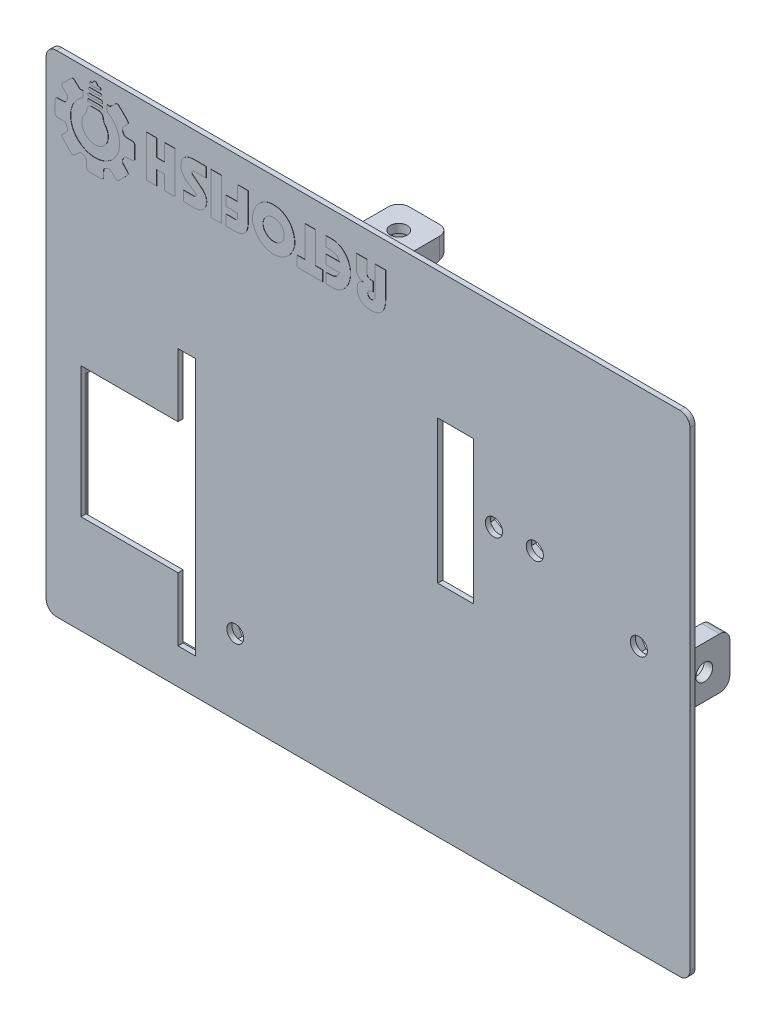
SolidWorks part; units mm, degrees
ref_plane "Front Plane" through (0, 0, 0) normal (0, 0, 1) x (1, 0, 0)
ref_plane "Top Plane" through (0, 0, 0) normal (0, 1, 0) x (1, 0, 0)
ref_plane "Right Plane" through (0, 0, 0) normal (1, 0, 0) x (0, 0, -1)
sketch "Sketch1" plane through (0, 0, 0) normal (0, 0, 1) x (1, 0, 0)
  line L1 (63, -48) -> (-63, -48)
  line L2 (63, -48) -> (63, 48)
  line L3 (63, 48) -> (-63, 48)
  line L4 (-63, -48) -> (-63, 48)
  line L5 (63, -48) -> (-63, 48) construction
  line L6 (63, 48) -> (-63, -48) construction
  circle A1 centre (53, 4) radius 1.675
  point P0 (0, 0)
  point P9 (0, 0)
  point P14 (0, 0)
  dimension "D4" = 52
  dimension "D3" = 10
  dimension "D1" = 126
  dimension "D2" = 96
extrude "Boss-Extrude1" add sketch "Sketch1" along normal blind 1
sketch "Sketch2" plane through (0, 0, 0) normal (0, 0, -1) x (-1, 0, 0)
  line L0 (-63, 48) -> (63, 48) construction
  line L1 (-59.8, 34.8) -> (-57.7, 34.8)
  line L2 (-59.8, 34.8) -> (-59.8, 44.8)
  line L3 (-59.8, 44.8) -> (-57.7, 44.8)
  line L4 (-57.7, 34.8) -> (-57.7, 44.8)
  line L5 (-59.8, 34.8) -> (-57.7, 44.8) construction
  line L6 (-59.8, 44.8) -> (-57.7, 34.8) construction
  line L7 (57.7, 34.8) -> (59.8, 34.8)
  line L8 (57.7, 34.8) -> (57.7, 44.8)
  line L9 (57.7, 44.8) -> (59.8, 44.8)
  line L10 (59.8, 34.8) -> (59.8, 44.8)
  line L11 (57.7, 34.8) -> (59.8, 44.8) construction
  line L12 (57.7, 44.8) -> (59.8, 34.8) construction
  line L13 (63, 48) -> (63, -48) construction
  line L14 (-63, -48) -> (-63, 48) construction
  line L15 (-59.8, -44.8) -> (-57.7, -44.8)
  line L16 (-59.8, -44.8) -> (-59.8, -34.8)
  line L17 (-59.8, -34.8) -> (-57.7, -34.8)
  line L18 (-57.7, -44.8) -> (-57.7, -34.8)
  line L19 (-59.8, -44.8) -> (-57.7, -34.8) construction
  line L20 (-59.8, -34.8) -> (-57.7, -44.8) construction
  line L21 (57.7, -44.8) -> (59.8, -44.8)
  line L22 (57.7, -44.8) -> (57.7, -34.8)
  line L23 (57.7, -34.8) -> (59.8, -34.8)
  line L24 (59.8, -44.8) -> (59.8, -34.8)
  line L25 (57.7, -44.8) -> (59.8, -34.8) construction
  line L26 (57.7, -34.8) -> (59.8, -44.8) construction
  line L27 (63, -48) -> (-63, -48) construction
  point P0 (-58.75, 39.8)
  point P5 (58.75, 39.8)
  point P12 (-58.75, -39.8)
  point P16 (0, 0)
  point P23 (58.75, -39.8)
  dimension "D1" = 2.1
  dimension "D3" = 10
  dimension "D4" = 10
  dimension "D5" = 3.2
  dimension "D6" = 3.2
  dimension "D7" = 3.2
  dimension "D8" = 3.2
  dimension "D11" = 10
  dimension "D12" = 10
  dimension "D13" = 3.2
  dimension "D14" = 3.2
  dimension "D15" = 3.2
  dimension "D16" = 3.2
extrude "Boss-Extrude2" add sketch "Sketch2" along normal blind 2.1 contours L1 L4 L2 | L4 L3 L2 | L10 L9 L8 | L7 L10 L8 | L15 L18 L17 L16 | L21 L24 L23 L22 region at (58.75, 39.8, 0) region at (-58.75, 39.8, 0)
sketch "Sketch3" plane through (-59.8, 0, 0) normal (-1, 0, 0) x (0, 0, 1)
  line L0 (-2.1, 34.8) -> (-2.1, 44.8) construction
  line L1 (-2.1, 44.8) -> (0, 44.8) construction
  circle A0 centre (2.9, 39.8) radius 1.675
  dimension "D1" = 5
  dimension "D2" = 5
  dimension "D3" = 3.35
chamfer "Chamfer1" distance 2 angle 45 4 edges at (57.7, 39.8, 0) (-57.7, 39.8, 0) (-57.7, -39.8, 0) (57.7, -39.8, 0)
sketch "Sketch5" plane through (59.8, 0, 0) normal (1, 0, 0) x (0, 0, -1)
  line L0 (2.1, -44.8) -> (2.1, -34.8) construction
  line L1 (2.1, -34.8) -> (0, -34.8) construction
  circle A0 centre (-2.9, -39.8) radius 1.675
  dimension "D1" = 5
  dimension "D2" = 5
  dimension "D3" = 3.35
sketch "Sketch7" plane through (0, 0, 1) normal (0, 0, 1) x (1, 0, 0)
  line L0 (63, -48) -> (63, 48) construction
  line L3 (63, 48) -> (-63, 48) construction
  circle A0 centre (32.63, 10) radius 1.675
  circle A1 centre (24.63, 10) radius 1.675
  dimension "D1" = 8
  dimension "D2" = 30.37
  dimension "D3" = 38
  dimension "3.3" = 3.35
extrude "Cut-Extrude5" cut sketch "Sketch7" against normal blind 10
sketch "Sketch9" plane through (0, 0, 1) normal (0, 0, 1) x (1, 0, 0)
  line L0 (63, 48) -> (-63, 48) construction
  line L1 (20.63, -5) -> (13.63, -5)
  line L2 (20.63, -5) -> (20.63, 23)
  line L3 (20.63, 23) -> (13.63, 23)
  line L4 (13.63, -5) -> (13.63, 23)
  line L5 (20.63, -5) -> (13.63, 23) construction
  line L6 (20.63, 23) -> (13.63, -5) construction
  line L8 (63, -48) -> (63, 48) construction
  point P0 (17.13, 9)
  dimension "D1" = 25
  dimension "D2" = 42.37
  dimension "D3" = 7
  dimension "D4" = 28
extrude "Cut-Extrude7" cut sketch "Sketch9" against normal blind 10
sketch "Sketch10" plane through (0, 0, 1) normal (0, 0, 1) x (1, 0, 0)
  point P0 (0, -22.5)
sketch "Sketch11" plane through (0, 0, 1) normal (0, 0, 1) x (1, 0, 0)
  line L1 (-63, -48) -> (63, -48) construction
  line L2 (63, -48) -> (63, 48) construction
  line L4 (-17, -20.2) -> (-8, -20.2)
  line L5 (-17, -20.2) -> (-17, -26.2)
  line L6 (-17, -26.2) -> (-8, -26.2)
  line L7 (-8, -20.2) -> (-8, -26.2)
  circle A1 centre (22, -36.45) radius 1.675
  circle A2 centre (22, -22.45) radius 1.675
  dimension "D1" = 9
  dimension "D2" = 6
  dimension "D3" = 71
  dimension "D4" = 41
  dimension "D5" = 11.55
  dimension "D8" = 41
  dimension "D9" = 3.35
  dimension "D10" = 14
  dimension "D7" = 27.8
extrude "Cut-Extrude8" cut sketch "Sketch11" against normal blind 10
sketch "Sketch21" plane through (0, 0, 0) normal (0, 0, -1) x (-1, 0, 0)
  line L7 (-50.7195, 7.95) -> (-55.2805, 7.95)
  line L8 (-55.2805, 7.95) -> (-57.5611, 4)
  line L9 (-57.5611, 4) -> (-55.2805, 0.05)
  line L10 (-55.2805, 0.05) -> (-50.7195, 0.05)
  line L11 (-50.7195, 0.05) -> (-48.4389, 4)
  line L12 (-48.4389, 4) -> (-50.7195, 7.95)
  line L13 (-51.3979, 6.775) -> (-54.6021, 6.775)
  line L14 (-54.6021, 6.775) -> (-56.2043, 4)
  line L15 (-56.2043, 4) -> (-54.6021, 1.225)
  line L16 (-54.6021, 1.225) -> (-51.3979, 1.225)
  line L17 (-51.3979, 1.225) -> (-49.7957, 4)
  line L18 (-49.7957, 4) -> (-51.3979, 6.775)
  line L25 (-21.83, 11.6166) -> (-24.63, 13.2332)
  line L26 (-24.63, 13.2332) -> (-27.43, 11.6166)
  line L27 (-27.43, 11.6166) -> (-27.43, 8.3834)
  line L28 (-27.43, 8.3834) -> (-24.63, 6.7668)
  line L29 (-24.63, 6.7668) -> (-21.83, 8.3834)
  line L30 (-21.83, 8.3834) -> (-21.83, 11.6166)
  line L31 (-20.68, 12.2805) -> (-24.63, 14.5611)
  line L32 (-24.63, 14.5611) -> (-28.58, 12.2805)
  line L33 (-28.58, 12.2805) -> (-28.58, 7.7195)
  line L34 (-28.58, 7.7195) -> (-24.63, 5.4389)
  line L35 (-24.63, 5.4389) -> (-20.68, 7.7195)
  line L36 (-20.68, 7.7195) -> (-20.68, 12.2805)
  line L37 (-29.83, 11.6166) -> (-32.63, 13.2332)
  line L38 (-32.63, 13.2332) -> (-35.43, 11.6166)
  line L39 (-35.43, 11.6166) -> (-35.43, 8.3834)
  line L40 (-35.43, 8.3834) -> (-32.63, 6.7668)
  line L41 (-32.63, 6.7668) -> (-29.83, 8.3834)
  line L42 (-29.83, 8.3834) -> (-29.83, 11.6166)
  line L43 (-28.68, 12.2805) -> (-32.63, 14.5611)
  line L44 (-32.63, 14.5611) -> (-36.58, 12.2805)
  line L45 (-36.58, 12.2805) -> (-36.58, 7.7195)
  line L46 (-36.58, 7.7195) -> (-32.63, 5.4389)
  line L47 (-32.63, 5.4389) -> (-28.68, 7.7195)
  line L48 (-28.68, 7.7195) -> (-28.68, 12.2805)
  line L76 (-63, 48) -> (63, 48) construction
  circle A1 centre (-53, 4) radius 3.95 construction
  circle A2 centre (-53, 4) radius 2.775 construction
  circle A4 centre (-24.63, 10) radius 2.8 construction
  circle A5 centre (-24.63, 10) radius 3.95 construction
  circle A6 centre (-32.63, 10) radius 2.8 construction
  circle A7 centre (-32.63, 10) radius 3.95 construction
  dimension "D1" = 5.6
  dimension "D2" = 7.9
extrude "Boss-Extrude3" add sketch "Sketch21" along normal blind 2
sketch "Sketch24" plane through (0, 0, 1) normal (0, 0, 1) x (1, 0, 0)
  line L0 (-63, 48) -> (-63, -48) construction
  line L1 (-56.2, -3.05) -> (-37.2, -3.05)
  line L2 (-56.2, -3.05) -> (-56.2, -28.65)
  line L3 (-56.2, -28.65) -> (-37.2, -28.65)
  line L4 (-37.2, -3.05) -> (-37.2, -28.65)
  line L5 (-56.2, -3.05) -> (-37.2, -28.65) construction
  line L6 (-56.2, -28.65) -> (-37.2, -3.05) construction
  line L11 (63, 48) -> (-63, 48) construction
  line L12 (-33.8, -41.05) -> (-37.2, -41.05)
  line L13 (-33.8, -41.05) -> (-33.8, 9.35)
  line L14 (-33.8, 9.35) -> (-37.2, 9.35)
  line L15 (-37.2, -41.05) -> (-37.2, 9.35)
  line L16 (-33.8, -41.05) -> (-37.2, 9.35) construction
  line L17 (-33.8, 9.35) -> (-37.2, -41.05) construction
  line L18 (-63, -48) -> (63, -48) construction
  circle A0 centre (-26, -33.35) radius 1.65
  point P0 (-46.7, -15.85)
  point P5 (-35.5, -15.85)
  dimension "D7" = 14.65
  dimension "D8" = 37
  dimension "D9" = 3.3
  dimension "D1" = 25.6
  dimension "D2" = 25.8
  dimension "D3" = 6.8
  dimension "D4" = 3.4
  dimension "D5" = 50.4
  dimension "D6" = 63.85
extrude "Cut-Extrude17" cut sketch "Sketch24" against normal blind 2 contours L4 L1 L2 L3 | L15 L12 L13 L14 L4 | A0 region at (-46.7, -15.85, 1) region at (-35.5, -15.85, 1) region at (-26, -33.35, 1)
sketch "Sketch26" plane through (0, 0, 0) normal (0, 0, -1) x (-1, 0, 0)
  line L0 (33.8, -28.2) -> (-57.8, -28.2)
  line L5 (-13.63, 23) -> (-13.63, -5) construction
  line L7 (33.8, -28.2) -> (33.8, -26.2)
  line L8 (-57.8, -28.2) -> (-57.8, -26.2)
  line L9 (33.8, -26.2) -> (-57.8, -26.2)
  line L10 (33.8, -41.05) -> (33.8, 9.35) construction
  line L11 (-6.63, -44.8) -> (-6.63, 45)
  line L12 (-6.63, -44.8) -> (-8.63, -44.8)
  line L13 (-6.63, 45) -> (-8.63, 45)
  line L14 (-8.63, -44.8) -> (-8.63, 45)
  line L15 (-57.8, -34.8) -> (-57.8, 34.8)
  line L16 (-57.8, -34.8) -> (-59.8, -34.8)
  line L17 (-57.8, 34.8) -> (-59.8, 34.8)
  line L18 (-59.8, -34.8) -> (-59.8, 34.8)
  line L19 (57.8, -34.8) -> (57.8, 34.8)
  line L20 (57.8, -34.8) -> (59.8, -34.8)
  line L21 (57.8, 34.8) -> (59.8, 34.8)
  line L22 (59.8, -34.8) -> (59.8, 34.8)
  line L23 (59.8, 43) -> (-59.8, 43)
  line L24 (59.8, 43) -> (59.8, 45)
  line L25 (-59.8, 43) -> (-59.8, 45)
  line L26 (59.8, 45) -> (-59.8, 45)
  line L31 (-57.8, -27.2) -> (33.8, -27.2) construction
  line L32 (17, -26.2) -> (8, -26.2) construction
  line L33 (-59.8, 34.8) -> (-55.7, 34.8) construction
  line L34 (-59.8, -34.8) -> (-55.7, -34.8) construction
  line L35 (-20.63, 23) -> (-13.63, 23) construction
  line L37 (59.8, 34.8) -> (59.8, 44.8) construction
  line L38 (57.8, 25) -> (-57.8, 25)
  line L39 (55.7, -34.8) -> (59.8, -34.8) construction
  line L40 (55.7, 34.8) -> (59.8, 34.8) construction
  line L43 (57.8, 25) -> (57.8, 23)
  line L44 (57.8, 23) -> (-57.8, 23)
  line L45 (-57.8, 25) -> (-57.8, 23)
  line L46 (57.7, -44.8) -> (-57.7, -44.8)
  line L47 (57.7, -44.8) -> (57.7, -42.8)
  line L48 (-57.7, -44.8) -> (-57.7, -42.8)
  line L49 (57.7, -42.8) -> (-57.7, -42.8)
  line L56 (-59.8, 34.8) -> (-59.8, 44.8) construction
  line L57 (-63, 48) -> (63, 48) construction
  line L58 (-59.8, -44.8) -> (-55.7, -44.8) construction
  line L59 (59.8, -44.8) -> (59.8, -34.8) construction
  line L60 (-57.7, -44.8) -> (-57.7, -34.8) construction
  line L61 (57.7, -34.8) -> (57.7, -44.8) construction
  point P0 (18, 0)
  dimension "D2" = 2
  dimension "D3" = 2
  dimension "D4" = 2
  dimension "D5" = 2
  dimension "D6" = 2
  dimension "D7" = 5
  dimension "D9" = 2
  dimension "D10" = 2
  dimension "D15" = 3
extrude "Boss-Extrude10" add sketch "Sketch26" along normal blind 2 contours L18 L16 L15 L8 L17 | L19 | L44 L38 L11 | L44 L14 L38 L15 | L0 L8 L9 L7 | L23 L25 L26 L24 | L46 L48 L49 L47 | L22 L21 L19 L20 | L14 L13 L11 L12 region at (58.8, 0, 0) region at (-25.585, 24, 0) region at (33.215, 24, 0)
fillet "Fillet2" radius 2 4 edges at (63, -48, 0.5) (63, 48, 0.5) (-63, 48, 0.5) (-63, -48, 0.5)
sketch "Sketch27" plane through (0, 0, 1) normal (0, 0, 1) x (1, 0, 0)
  line L1 (-20.9274, -16.1259) -> (30.4399, -16.1259)
  line L2 (-20.9274, -16.1259) -> (-20.9274, -40.4054)
  line L3 (-20.9274, -40.4054) -> (30.4399, -40.4054)
  line L4 (30.4399, -16.1259) -> (30.4399, -40.4054)
extrude "Boss-Extrude11" add sketch "Sketch27" against normal up to surface (1 mm away) up to face at (-24.35, -33.35, 0)
sketch "Sketch28" plane through (0, 0, 0) normal (0, 0, -1) x (-1, 0, 0)
  line L0 (-55.2805, 0.05) -> (-50.7195, 0.05) construction
  line L1 (27.6021, -30.575) -> (24.3979, -30.575)
  line L2 (24.3979, -30.575) -> (22.7957, -33.35)
  line L3 (22.7957, -33.35) -> (24.3979, -36.125)
  line L4 (24.3979, -36.125) -> (27.6021, -36.125)
  line L5 (27.6021, -36.125) -> (29.2043, -33.35)
  line L6 (29.2043, -33.35) -> (27.6021, -30.575)
  line L7 (28.2805, -29.4) -> (23.7195, -29.4)
  line L8 (23.7195, -29.4) -> (21.4389, -33.35)
  line L9 (21.4389, -33.35) -> (23.7195, -37.3)
  line L10 (23.7195, -37.3) -> (28.2805, -37.3)
  line L11 (28.2805, -37.3) -> (30.5611, -33.35)
  line L12 (30.5611, -33.35) -> (28.2805, -29.4)
  line L13 (-51.3979, 6.775) -> (-54.6021, 6.775) construction
  line L14 (-50.7195, 7.95) -> (-55.2805, 7.95) construction
  circle A0 centre (26, -33.35) radius 2.775 construction
  circle A1 centre (26, -33.35) radius 3.95 construction
extrude "Boss-Extrude12" add sketch "Sketch28" along normal up to surface (2 mm away) up to face at (53, 4, -2)
sketch "Sketch29" plane through (0, 0, 1) normal (0, 0, 1) x (1, 0, 0)
  line L0 (-52.3355, 41.8994) -> (-52.504, 41.9799)
  line L1 (-52.504, 41.9799) -> (-53.386, 41.9799)
  line L2 (-53.386, 41.9799) -> (-54.268, 41.9799)
  line L3 (-54.268, 41.9799) -> (-54.4366, 41.8994)
  line L4 (-52.2055, 44.9577) -> (-52.2814, 45.0336)
  line L5 (-52.2814, 45.0336) -> (-53.3967, 45.0336)
  line L6 (-53.3967, 45.0336) -> (-54.5115, 45.0336)
  line L7 (-54.5115, 45.0336) -> (-54.5928, 44.9635)
  line L8 (-51.9921, 43.9252) -> (-52.0681, 44.0012)
  line L9 (-52.0681, 44.0012) -> (-53.3834, 44.0012)
  line L10 (-53.3834, 44.0012) -> (-54.6981, 44.0012)
  line L11 (-54.6981, 44.0012) -> (-54.7795, 43.9311)
  line L12 (-51.9921, 42.9308) -> (-52.0681, 43.0067)
  line L13 (-52.0681, 43.0067) -> (-53.3834, 43.0067)
  line L14 (-53.3834, 43.0067) -> (-54.6981, 43.0067)
  line L15 (-54.6981, 43.0067) -> (-54.7795, 42.9366)
  line L16 (-46.6367, 36.76) -> (-45.9154, 36.7731)
  line L17 (-45.9154, 36.7731) -> (-45.816, 36.8394)
  line L18 (-45.6546, 37.0326) -> (-45.5954, 37.1608)
  line L19 (-45.5954, 37.1608) -> (-45.5954, 38.4325)
  line L20 (-45.5954, 38.4325) -> (-45.5954, 39.701)
  line L21 (-45.5954, 39.701) -> (-45.6567, 39.8261)
  line L22 (-45.8187, 40.0177) -> (-45.9162, 40.0866)
  line L23 (-45.9162, 40.0866) -> (-46.6367, 40.0997)
  line L24 (-50.9879, 43.8567) -> (-51.042, 43.882)
  line L25 (-51.042, 43.882) -> (-51.042, 43.2945)
  line L26 (-60.1618, 40.1023) -> (-60.8831, 40.0867)
  line L27 (-60.8831, 40.0867) -> (-60.9779, 40.0226)
  line L28 (-61.1393, 39.8314) -> (-61.2033, 39.701)
  line L29 (-61.2033, 39.701) -> (-61.2033, 38.4325)
  line L30 (-61.2033, 38.4325) -> (-61.2033, 37.1608)
  line L31 (-61.2033, 37.1608) -> (-61.1441, 37.0326)
  line L32 (-60.9827, 36.8394) -> (-60.8833, 36.7731)
  line L33 (-60.8833, 36.7731) -> (-60.1619, 36.76)
  line L34 (-55.0692, 31.6539) -> (-55.0561, 30.9461)
  line L35 (-55.0561, 30.9461) -> (-54.9921, 30.8513)
  line L36 (-54.8009, 30.6899) -> (-54.6705, 30.6259)
  line L37 (-54.6705, 30.6259) -> (-53.402, 30.6286)
  line L38 (-46.6372, 36.7852) -> (-45.9233, 36.7982)
  line L39 (-45.9233, 36.7982) -> (-45.8302, 36.8602)
  line L40 (-45.6774, 37.0433) -> (-45.6206, 37.1663)
  line L41 (-45.6206, 37.1663) -> (-45.6206, 38.4325)
  line L42 (-45.6206, 38.4325) -> (-45.6206, 39.6951)
  line L43 (-45.6206, 39.6951) -> (-45.6793, 39.8149)
  line L44 (-45.8329, 39.9969) -> (-45.9244, 40.0616)
  line L45 (-45.9244, 40.0616) -> (-46.6372, 40.0745)
  line L46 (-50.9984, 43.8337) -> (-51.0168, 43.8423)
  line L47 (-51.0168, 43.8423) -> (-51.0168, 43.2945)
  line L48 (-60.1612, 40.0771) -> (-60.8751, 40.0616)
  line L49 (-60.8751, 40.0616) -> (-60.9638, 40.0017)
  line L50 (-61.1167, 39.8202) -> (-61.1781, 39.6951)
  line L51 (-61.1781, 39.6951) -> (-61.1781, 38.4325)
  line L52 (-61.1781, 38.4325) -> (-61.1781, 37.1663)
  line L53 (-61.1781, 37.1663) -> (-61.1213, 37.0433)
  line L54 (-60.9685, 36.8602) -> (-60.8755, 36.7982)
  line L55 (-60.8755, 36.7982) -> (-60.1614, 36.7852)
  line L56 (-55.044, 31.6544) -> (-55.0311, 30.954)
  line L57 (-55.0311, 30.954) -> (-54.9713, 30.8654)
  line L58 (-54.7897, 30.7125) -> (-54.6647, 30.6512)
  line L59 (-54.6647, 30.6512) -> (-53.402, 30.6538)
  line L60 (-52.3464, 41.8767) -> (-52.5097, 41.9547)
  line L61 (-52.5097, 41.9547) -> (-53.386, 41.9547)
  line L62 (-53.386, 41.9547) -> (-54.2623, 41.9547)
  line L63 (-54.2623, 41.9547) -> (-54.4258, 41.8766)
  line L64 (-52.01, 42.913) -> (-52.0785, 42.9815)
  line L65 (-52.0785, 42.9815) -> (-53.3834, 42.9815)
  line L66 (-53.3834, 42.9815) -> (-54.6888, 42.9815)
  line L67 (-54.6888, 42.9815) -> (-54.7629, 42.9177)
  line L68 (-52.01, 43.9074) -> (-52.0785, 43.976)
  line L69 (-52.0785, 43.976) -> (-53.3834, 43.976)
  line L70 (-53.3834, 43.976) -> (-54.6888, 43.976)
  line L71 (-54.6888, 43.976) -> (-54.7629, 43.9122)
  line L72 (-52.2233, 44.9399) -> (-52.2919, 45.0084)
  line L73 (-52.2919, 45.0084) -> (-53.3967, 45.0084)
  line L74 (-53.3967, 45.0084) -> (-54.5021, 45.0084)
  line L75 (-54.5021, 45.0084) -> (-54.5762, 44.9446)
  spline S0 degree 3 poles (-54.4366, 41.8994) (-54.5178, 41.8612) (-54.6782, 41.7629) (-54.8392, 41.5798) (-54.9479, 41.3528) (-54.9858, 41.1456) (-54.9947, 41.0469) knots -0.000046 -0.000046 -0.000046 -0.000046 0.249973 0.499993 0.750012 1.000031 1.000031 1.000031 1.000031
  spline S1 degree 3 poles (-54.9947, 41.0469) (-55.0032, 40.9545) (-55.0291, 40.7611) (-55.1072, 40.5332) (-55.2273, 40.3283) (-55.361, 40.142) (-55.4505, 40.0264) (-55.4934, 39.9722) knots -0.000035 -0.000035 -0.000035 -0.000035 0.249965 0.499966 0.749966 0.874966 0.999966 0.999966 0.999966 0.999966
  spline S2 degree 3 poles (-55.4934, 39.9722) (-55.538, 39.9153) (-55.6187, 39.7997) (-55.7343, 39.5948) (-55.8344, 39.3728) (-55.89, 39.2147) (-55.9141, 39.1353) knots 0.000077 0.000077 0.000077 0.000077 0.250072 0.500067 0.750063 1.000058 1.000058 1.000058 1.000058
  spline S3 degree 3 poles (-55.9141, 39.1353) (-55.9285, 39.0882) (-55.9587, 38.9859) (-55.9771, 38.8769) (-55.9846, 38.7369) (-55.9864, 38.58) (-55.9866, 38.4682) (-55.9866, 38.4165) knots -0.00008 -0.00008 -0.00008 -0.00008 0.24994 0.49996 0.74998 0.87499 1 1 1 1
  spline S4 degree 3 poles (-55.9866, 38.4165) (-55.9866, 38.365) (-55.9864, 38.2539) (-55.9846, 38.097) (-55.9774, 37.9566) (-55.9595, 37.8475) (-55.9307, 37.7488) (-55.9168, 37.7032) knots 0 0 0 0 0.124986 0.249972 0.499943 0.749915 0.999887 0.999887 0.999887 0.999887
  spline S5 degree 3 poles (-55.9168, 37.7032) (-55.8938, 37.6287) (-55.8418, 37.4865) (-55.737, 37.2529) (-55.6166, 37.0315) (-55.5412, 36.9154) (-55.4978, 36.857) knots 0.000095 0.000095 0.000095 0.000095 0.250106 0.500117 0.750127 1.000138 1.000138 1.000138 1.000138
  spline S6 degree 3 poles (-55.4978, 36.857) (-55.3586, 36.6681) (-55.0234, 36.3271) (-54.4128, 35.9767) (-53.7294, 35.793) (-53.2424, 35.7953) (-53.0064, 35.8287) knots -0.000037 -0.000037 -0.000037 -0.000037 0.24997 0.499977 0.749983 0.99999 0.99999 0.99999 0.99999
  spline S7 degree 3 poles (-53.0064, 35.8287) (-52.8309, 35.8538) (-52.4882, 35.9451) (-51.9971, 36.1935) (-51.5619, 36.5368) (-51.3262, 36.8159) (-51.2251, 36.9669) knots 0.000014 0.000014 0.000014 0.000014 0.24999 0.499967 0.749943 0.99992 0.99992 0.99992 0.99992
  spline S8 degree 3 poles (-51.2251, 36.9669) (-51.1872, 37.0244) (-51.1114, 37.1455) (-51.0271, 37.3088) (-50.9543, 37.4835) (-50.9041, 37.636) (-50.8819, 37.7086) knots 0.000188 0.000188 0.000188 0.000188 0.250177 0.500166 0.750155 1.000144 1.000144 1.000144 1.000144
  spline S9 degree 3 poles (-50.8819, 37.7086) (-50.8679, 37.7533) (-50.8392, 37.8497) (-50.8213, 37.9582) (-50.8141, 38.0983) (-50.8123, 38.2547) (-50.8121, 38.3653) (-50.8121, 38.4165) knots -0.000217 -0.000217 -0.000217 -0.000217 0.249837 0.499891 0.749946 0.874973 1 1 1 1
  spline S10 degree 3 poles (-50.8121, 38.4165) (-50.8121, 38.4683) (-50.8123, 38.58) (-50.8141, 38.7373) (-50.8213, 38.8777) (-50.8392, 38.9867) (-50.868, 39.0865) (-50.8819, 39.1325) knots 0 0 0 0 0.124966 0.249933 0.499865 0.749798 0.99973 0.99973 0.99973 0.99973
  spline S11 degree 3 poles (-50.8819, 39.1325) (-50.9067, 39.2125) (-50.9636, 39.3635) (-51.0811, 39.6169) (-51.2158, 39.854) (-51.2932, 39.9675) (-51.3397, 40.0252) knots 0.00022 0.00022 0.00022 0.00022 0.250216 0.500211 0.750207 1.000202 1.000202 1.000202 1.000202
  spline S12 degree 3 poles (-51.3397, 40.0252) (-51.3766, 40.0714) (-51.4527, 40.1694) (-51.5691, 40.3342) (-51.6756, 40.5236) (-51.7359, 40.7185) (-51.7653, 40.8923) (-51.7759, 40.9952) (-51.7801, 41.0448) knots -0.000102 -0.000102 -0.000102 -0.000102 0.124929 0.24996 0.500021 0.750083 0.875114 1.000144 1.000144 1.000144 1.000144
  spline S13 degree 3 poles (-51.7801, 41.0448) (-51.7835, 41.0901) (-51.7927, 41.1891) (-51.8096, 41.2858) (-51.8326, 41.3664) (-51.8558, 41.4196) (-51.8684, 41.4454) knots -0.000267 -0.000267 -0.000267 -0.000267 0.249732 0.499731 0.74973 0.999729 0.999729 0.999729 0.999729
  spline S14 degree 3 poles (-51.8684, 41.4454) (-51.8925, 41.4941) (-51.9493, 41.5872) (-52.0584, 41.7123) (-52.1874, 41.8187) (-52.285, 41.8754) (-52.3355, 41.8994) knots 0.000158 0.000158 0.000158 0.000158 0.250127 0.500096 0.750065 1.000034 1.000034 1.000034 1.000034
  spline S15 degree 3 poles (-52.3739, 45.5372) (-52.3563, 45.5477) (-52.3219, 45.5729) (-52.2885, 45.619) (-52.2668, 45.6759) (-52.2608, 45.7318) (-52.2603, 45.7577) knots 0.006401 0.006401 0.006401 0.006401 0.255102 0.503803 0.752504 1.001206 1.001206 1.001206 1.001206
  spline S16 degree 3 poles (-52.2603, 45.7577) (-52.2592, 45.7835) (-52.2602, 45.8407) (-52.2745, 45.8939) (-52.2999, 45.9404) (-52.3359, 45.9778) (-52.3535, 45.9938) knots -0.001199 -0.001199 -0.001199 -0.001199 0.249371 0.499941 0.750511 1.001081 1.001081 1.001081 1.001081
  spline S17 degree 3 poles (-52.3535, 45.9938) (-52.3614, 46.0012) (-52.3767, 46.0127) (-52.4208, 46.0275) (-52.4932, 46.0387) (-52.5833, 46.0449) (-52.6232, 46.0471) knots -0.001587 -0.001587 -0.001587 -0.001587 0.248739 0.499065 0.749392 0.999718 0.999718 0.999718 0.999718
  spline S18 degree 3 poles (-52.6232, 46.0471) (-52.6677, 46.0493) (-52.7708, 46.0557) (-52.8404, 46.0643) (-52.9073, 46.097) (-52.9205, 46.1368) (-52.9238, 46.1566) knots 0.000245 0.000245 0.000245 0.000245 0.251684 0.503123 0.754563 1.006002 1.006002 1.006002 1.006002
  spline S19 degree 3 poles (-52.9238, 46.1566) (-52.9276, 46.1843) (-52.9376, 46.2464) (-52.9548, 46.2965) (-52.9791, 46.3398) (-53.015, 46.3818) (-53.0317, 46.4001) knots -0.001538 -0.001538 -0.001538 -0.001538 0.249242 0.500023 0.750803 1.001583 1.001583 1.001583 1.001583
  spline S20 degree 3 poles (-53.0317, 46.4001) (-53.0783, 46.454) (-53.1992, 46.5492) (-53.386, 46.5881) (-53.5728, 46.5492) (-53.6937, 46.454) (-53.7404, 46.4001) knots -0.000592 -0.000592 -0.000592 -0.000592 0.249704 0.5 0.750296 1.000592 1.000592 1.000592 1.000592
  spline S21 degree 3 poles (-53.7404, 46.4001) (-53.7571, 46.3818) (-53.793, 46.3398) (-53.8172, 46.2965) (-53.8344, 46.2464) (-53.8444, 46.1843) (-53.8483, 46.1566) knots -0.001583 -0.001583 -0.001583 -0.001583 0.249198 0.499979 0.75076 1.001541 1.001541 1.001541 1.001541
  spline S22 degree 3 poles (-53.8483, 46.1566) (-53.8516, 46.1364) (-53.8668, 46.0954) (-53.9322, 46.0655) (-53.9988, 46.0582) (-54.0793, 46.052) (-54.1357, 46.0487) (-54.1619, 46.0472) knots -0.006038 -0.006038 -0.006038 -0.006038 0.245488 0.497014 0.748539 0.874302 1.000065 1.000065 1.000065 1.000065
  spline S23 degree 3 poles (-54.1619, 46.0472) (-54.1886, 46.0457) (-54.2462, 46.0423) (-54.3264, 46.0363) (-54.3891, 46.0261) (-54.4242, 46.0112) (-54.4551, 45.9834) (-54.4685, 45.9705) knots -0.000062 -0.000062 -0.000062 -0.000062 0.124957 0.249976 0.500015 0.750053 1.000092 1.000092 1.000092 1.000092
  spline S24 degree 3 poles (-54.4685, 45.9705) (-54.4816, 45.9579) (-54.5105, 45.9278) (-54.5251, 45.9009) (-54.5341, 45.8694) (-54.5358, 45.8219) (-54.5358, 45.8014) knots -0.000104 -0.000104 -0.000104 -0.000104 0.249922 0.499948 0.749974 1 1 1 1
  spline S25 degree 3 poles (-54.5358, 45.8014) (-54.5358, 45.768) (-54.5308, 45.6952) (-54.509, 45.6234) (-54.4764, 45.572) (-54.4452, 45.5494) (-54.4285, 45.5403) knots 0 0 0 0 0.249288 0.498577 0.747865 0.997153 0.997153 0.997153 0.997153
  spline S26 degree 3 poles (-54.4285, 45.5403) (-54.4142, 45.5369) (-54.3939, 45.5338) (-54.2812, 45.5235) (-54.08, 45.5149) (-53.7611, 45.5078) (-53.4065, 45.5051) (-53.0511, 45.5066) (-52.7314, 45.5125) (-52.5254, 45.5209) (-52.4142, 45.5301) (-52.3897, 45.5337) (-52.3739, 45.5372) knots 0.023161 0.023161 0.023161 0.023161 0.0824 0.14164 0.260119 0.378598 0.497077 0.615557 0.734036 0.852515 0.911754 0.970994 0.970994 0.970994 0.970994
  spline S27 degree 3 poles (-54.5928, 44.9635) (-54.6083, 44.9496) (-54.6438, 44.9155) (-54.6588, 44.8898) (-54.6677, 44.8609) (-54.6691, 44.8096) (-54.6691, 44.788) knots 0.001503 0.001503 0.001503 0.001503 0.251127 0.500751 0.750376 1 1 1 1
  spline S28 degree 3 poles (-54.6691, 44.788) (-54.6691, 44.771) (-54.6675, 44.7377) (-54.6613, 44.6834) (-54.651, 44.6356) (-54.6464, 44.6212) (-54.6421, 44.6125) knots 0 0 0 0 0.2514 0.5028 0.7542 1.0056 1.0056 1.0056 1.0056
  spline S29 degree 3 poles (-54.6421, 44.6125) (-54.6357, 44.5988) (-54.6209, 44.5678) (-54.6009, 44.5477) (-54.5631, 44.5294) (-54.4732, 44.5123) (-54.3268, 44.502) (-54.1108, 44.4964) (-53.8592, 44.4948) (-53.6136, 44.4944) (-53.4651, 44.4943) (-53.3941, 44.4943) knots -0.00138 -0.00138 -0.00138 -0.00138 0.123789 0.248959 0.374128 0.499298 0.624468 0.749637 0.874807 0.937392 0.999976 0.999976 0.999976 0.999976
  spline S30 degree 3 poles (-53.3941, 44.4943) (-53.311, 44.4946) (-53.1373, 44.4954) (-52.8506, 44.4976) (-52.5617, 44.5018) (-52.3741, 44.5084) (-52.2812, 44.5155) (-52.2613, 44.5184) (-52.2483, 44.5211) knots 0.000038 0.000038 0.000038 0.000038 0.11625 0.232461 0.464885 0.697309 0.813521 0.929733 0.929733 0.929733 0.929733
  spline S31 degree 3 poles (-52.2483, 44.5211) (-52.2289, 44.5319) (-52.1897, 44.5586) (-52.156, 44.6048) (-52.1346, 44.6639) (-52.1296, 44.7291) (-52.1296, 44.7586) knots 0.001931 0.001931 0.001931 0.001931 0.251448 0.500965 0.750483 1 1 1 1
  spline S32 degree 3 poles (-52.1296, 44.7586) (-52.1296, 44.7833) (-52.131, 44.8412) (-52.1404, 44.8766) (-52.156, 44.9061) (-52.1903, 44.9425) (-52.2055, 44.9577) knots 0 0 0 0 0.25 0.5 0.75 1 1 1 1
  spline S33 degree 3 poles (-54.7795, 43.9311) (-54.795, 43.9171) (-54.8308, 43.8831) (-54.8454, 43.8581) (-54.8544, 43.8292) (-54.8558, 43.7755) (-54.8558, 43.7529) knots 0.001495 0.001495 0.001495 0.001495 0.251121 0.500747 0.750374 1 1 1 1
  spline S34 degree 3 poles (-54.8558, 43.7529) (-54.8558, 43.7209) (-54.8493, 43.6533) (-54.8226, 43.5759) (-54.7837, 43.5186) (-54.7531, 43.4967) (-54.7358, 43.4878) knots 0 0 0 0 0.247513 0.495027 0.74254 0.990053 0.990053 0.990053 0.990053
  spline S35 degree 3 poles (-54.7358, 43.4878) (-54.7172, 43.4848) (-54.6912, 43.4824) (-54.546, 43.4743) (-54.2818, 43.4677) (-53.8597, 43.4625) (-53.3886, 43.461) (-52.9171, 43.4628) (-52.4935, 43.4683) (-52.2271, 43.4753) (-52.08, 43.4838) (-52.0525, 43.4865) (-52.0332, 43.4896) knots 0.023969 0.023969 0.023969 0.023969 0.083123 0.142277 0.260585 0.378892 0.4972 0.615508 0.733816 0.852123 0.911277 0.970431 0.970431 0.970431 0.970431
  spline S36 degree 3 poles (-52.0332, 43.4896) (-52.0141, 43.5004) (-51.9757, 43.5268) (-51.9423, 43.573) (-51.9212, 43.6319) (-51.9162, 43.6968) (-51.9162, 43.7262) knots 0.007864 0.007864 0.007864 0.007864 0.255898 0.503932 0.751966 1 1 1 1
  spline S37 degree 3 poles (-51.9162, 43.7262) (-51.9162, 43.7509) (-51.9176, 43.8088) (-51.9271, 43.8441) (-51.9426, 43.8737) (-51.977, 43.9101) (-51.9921, 43.9252) knots 0 0 0 0 0.25 0.5 0.75 1 1 1 1
  spline S38 degree 3 poles (-54.7795, 42.9366) (-54.795, 42.9226) (-54.8308, 42.8886) (-54.8454, 42.8636) (-54.8544, 42.8348) (-54.8558, 42.781) (-54.8558, 42.7584) knots 0.001495 0.001495 0.001495 0.001495 0.251121 0.500747 0.750374 1 1 1 1
  spline S39 degree 3 poles (-54.8558, 42.7584) (-54.8558, 42.7253) (-54.85, 42.6543) (-54.8255, 42.5792) (-54.7893, 42.5254) (-54.7579, 42.5041) (-54.7407, 42.4958) knots 0 0 0 0 0.248876 0.497751 0.746627 0.995502 0.995502 0.995502 0.995502
  spline S40 degree 3 poles (-54.7407, 42.4958) (-54.7225, 42.4925) (-54.6973, 42.4901) (-54.5522, 42.4812) (-54.2878, 42.4739) (-53.8648, 42.468) (-53.3926, 42.4658) (-52.9197, 42.4673) (-52.4949, 42.4727) (-52.2277, 42.4799) (-52.0801, 42.4888) (-52.0528, 42.4916) (-52.0336, 42.4949) knots 0.022815 0.022815 0.022815 0.022815 0.082071 0.141327 0.25984 0.378353 0.496866 0.615379 0.733891 0.852404 0.911661 0.970917 0.970917 0.970917 0.970917
  spline S41 degree 3 poles (-52.0336, 42.4949) (-52.0145, 42.5057) (-51.9759, 42.5321) (-51.9424, 42.5784) (-51.9212, 42.6373) (-51.9162, 42.7023) (-51.9162, 42.7317) knots 0.006322 0.006322 0.006322 0.006322 0.254742 0.503161 0.751581 1 1 1 1
  spline S42 degree 3 poles (-51.9162, 42.7317) (-51.9162, 42.7564) (-51.9176, 42.8143) (-51.9271, 42.8496) (-51.9426, 42.8792) (-51.977, 42.9156) (-51.9921, 42.9308) knots 0 0 0 0 0.25 0.5 0.75 1 1 1 1
  spline S43 degree 3 poles (-45.816, 36.8394) (-45.7989, 36.8512) (-45.7655, 36.8771) (-45.7239, 36.9199) (-45.6874, 36.9694) (-45.6644, 37.0117) (-45.6546, 37.0326) knots 0.001432 0.001432 0.001432 0.001432 0.251178 0.500925 0.750671 1.000417 1.000417 1.000417 1.000417
  spline S44 degree 3 poles (-45.6567, 39.8261) (-45.6667, 39.8459) (-45.6889, 39.8842) (-45.7291, 39.9381) (-45.7739, 39.9846) (-45.8028, 40.0072) (-45.8187, 40.0177) knots -0.000393 -0.000393 -0.000393 -0.000393 0.25058 0.501554 0.752527 1.0035 1.0035 1.0035 1.0035
  spline S45 degree 3 poles (-46.6367, 40.0997) (-46.6857, 40.1006) (-46.788, 40.1026) (-46.9582, 40.1065) (-47.135, 40.1122) (-47.2937, 40.1229) (-47.453, 40.1457) (-47.5845, 40.2001) (-47.6632, 40.2896) (-47.7009, 40.3333) knots -0.000028 -0.000028 -0.000028 -0.000028 0.062487 0.125003 0.250033 0.375063 0.500093 0.750154 1.000215 1.000215 1.000215 1.000215
  spline S46 degree 3 poles (-47.7009, 40.3333) (-47.7372, 40.376) (-47.7911, 40.4619) (-47.8915, 40.6578) (-47.9748, 40.868) (-48.0079, 40.9786) (-48.0189, 41.0395) knots -0.000387 -0.000387 -0.000387 -0.000387 0.249492 0.499372 0.749252 0.999131 0.999131 0.999131 0.999131
  spline S47 degree 3 poles (-48.0189, 41.0395) (-48.0229, 41.06) (-48.0277, 41.1003) (-48.0293, 41.169) (-48.0254, 41.2386) (-48.0198, 41.2804) (-48.0161, 41.3017) knots 0.002368 0.002368 0.002368 0.002368 0.253295 0.504222 0.755148 1.006075 1.006075 1.006075 1.006075
  spline S48 degree 3 poles (-48.0161, 41.3017) (-48.0086, 41.3338) (-47.9907, 41.3924) (-47.9194, 41.4954) (-47.7958, 41.6298) (-47.6447, 41.7849) (-47.5356, 41.895) (-47.4851, 41.9458) knots -0.003933 -0.003933 -0.003933 -0.003933 0.247043 0.498019 0.748995 0.874483 0.99997 0.99997 0.99997 0.99997
  spline S49 degree 3 poles (-47.4851, 41.9458) (-47.4282, 42.0033) (-47.3068, 42.1271) (-47.1326, 42.3115) (-46.9866, 42.485) (-46.9133, 42.619) (-46.9029, 42.6944) (-46.9023, 42.7348) knots 0.000026 0.000026 0.000026 0.000026 0.124943 0.249859 0.499692 0.749525 0.999358 0.999358 0.999358 0.999358
  spline S50 degree 3 poles (-46.9023, 42.7348) (-46.9023, 42.7608) (-46.9028, 42.8172) (-46.9167, 42.8946) (-46.9703, 42.9923) (-47.1186, 43.1649) (-47.2853, 43.342) (-47.4815, 43.5424) (-47.6734, 43.7365) (-47.7895, 43.8536) (-47.8451, 43.9097) knots 0.000455 0.000455 0.000455 0.000455 0.125397 0.250339 0.500223 0.625165 0.750107 0.875049 0.93752 0.999991 0.999991 0.999991 0.999991
  spline S51 degree 3 poles (-47.8451, 43.9097) (-47.9607, 44.0259) (-48.2034, 44.2684) (-48.5049, 44.5649) (-48.6898, 44.7433) (-48.79, 44.8348) (-48.8043, 44.8478) (-48.8171, 44.857) knots 0.000018 0.000018 0.000018 0.000018 0.245051 0.490084 0.735118 0.857634 0.980151 0.980151 0.980151 0.980151
  spline S52 degree 3 poles (-48.8171, 44.857) (-48.8442, 44.8737) (-48.8996, 44.8967) (-49.0142, 44.9209) (-49.1326, 44.9231) (-49.1947, 44.9129) (-49.2262, 44.9026) knots -0.000665 -0.000665 -0.000665 -0.000665 0.249725 0.500115 0.750505 1.000894 1.000894 1.000894 1.000894
  spline S53 degree 3 poles (-49.2262, 44.9026) (-49.2481, 44.8958) (-49.2734, 44.8803) (-49.3894, 44.7906) (-49.5277, 44.6625) (-49.6709, 44.525) (-49.761, 44.4366) (-49.8036, 44.3947) knots -0.00133 -0.00133 -0.00133 -0.00133 0.249012 0.499355 0.749698 0.874869 1.000041 1.000041 1.000041 1.000041
  spline S54 degree 3 poles (-49.8036, 44.3947) (-49.8697, 44.3298) (-50.008, 44.1963) (-50.1879, 44.0282) (-50.3039, 43.9246) (-50.3696, 43.8713) (-50.3893, 43.8567) (-50.4021, 43.85) knots -0.000057 -0.000057 -0.000057 -0.000057 0.249885 0.499826 0.749767 0.874738 0.999708 0.999708 0.999708 0.999708
  spline S55 degree 3 poles (-50.4021, 43.85) (-50.4428, 43.8284) (-50.5292, 43.8023) (-50.6848, 43.7902) (-50.8452, 43.8076) (-50.9415, 43.8362) (-50.9879, 43.8567) knots 0.000147 0.000147 0.000147 0.000147 0.250375 0.500603 0.750831 1.001059 1.001059 1.001059 1.001059
  spline S56 degree 3 poles (-51.042, 43.2945) (-51.042, 43.2196) (-51.0423, 43.0628) (-51.0432, 42.8699) (-51.0446, 42.7103) (-51.0455, 42.6599) (-51.0463, 42.6278) knots 0 0 0 0 0.214168 0.428337 0.642505 0.856674 0.856674 0.856674 0.856674
  spline S57 degree 3 poles (-51.0463, 42.6278) (-51.031, 42.6153) (-51.004, 42.5938) (-50.9387, 42.5459) (-50.858, 42.4888) (-50.794, 42.445) (-50.763, 42.4242) knots 0.237673 0.237673 0.237673 0.237673 0.428232 0.618791 0.80935 0.999909 0.999909 0.999909 0.999909
  spline S58 degree 3 poles (-50.763, 42.4242) (-50.5356, 42.2722) (-50.0968, 41.9284) (-49.566, 41.3445) (-49.1426, 40.6827) (-48.9312, 40.1787) (-48.8469, 39.9232) knots 0.000017 0.000017 0.000017 0.000017 0.250009 0.500001 0.749994 0.999986 0.999986 0.999986 0.999986
  spline S59 degree 3 poles (-48.8469, 39.9232) (-48.7677, 39.6844) (-48.647, 39.1901) (-48.5679, 38.2018) (-48.7546, 36.9787) (-49.2968, 35.8668) (-49.9238, 35.0994) (-50.3039, 34.7616) (-50.5047, 34.6104) knots 0.000008 0.000008 0.000008 0.000008 0.125007 0.250007 0.500007 0.750006 0.875006 1.000005 1.000005 1.000005 1.000005
  spline S60 degree 3 poles (-50.5047, 34.6104) (-50.7009, 34.4631) (-51.1195, 34.1963) (-52.0012, 33.8081) (-53.1773, 33.5812) (-54.3695, 33.7078) (-55.2829, 34.0202) (-55.7243, 34.251) (-55.933, 34.3812) knots -0.000006 -0.000006 -0.000006 -0.000006 0.124995 0.249995 0.499996 0.749997 0.874997 0.999997 0.999997 0.999997 0.999997
  spline S61 degree 3 poles (-55.933, 34.3812) (-56.1608, 34.5232) (-56.5953, 34.8499) (-57.3184, 35.6188) (-57.9591, 36.7712) (-58.2024, 38.0686) (-58.1377, 39.1252) (-58.0122, 39.6566) (-57.9278, 39.9124) knots 0.000002 0.000002 0.000002 0.000002 0.125001 0.249999 0.499997 0.749994 0.874992 0.999991 0.999991 0.999991 0.999991
  spline S62 degree 3 poles (-57.9278, 39.9124) (-57.8447, 40.1664) (-57.6353, 40.6648) (-57.2116, 41.3319) (-56.6837, 41.9201) (-56.2603, 42.2567) (-56.0383, 42.4056) knots 0.000018 0.000018 0.000018 0.000018 0.250027 0.500036 0.750045 1.000054 1.000054 1.000054 1.000054
  spline S63 degree 3 poles (-56.0383, 42.4056) (-56.0078, 42.4257) (-55.9447, 42.4672) (-55.8626, 42.5203) (-55.7946, 42.5632) (-55.7649, 42.5807) (-55.7479, 42.5904) knots -0.000318 -0.000318 -0.000318 -0.000318 0.209989 0.420296 0.630603 0.84091 0.84091 0.84091 0.84091
  spline S64 degree 3 poles (-45.8302, 36.8602) (-45.8139, 36.8714) (-45.7821, 36.8962) (-45.7432, 36.9363) (-45.7089, 36.9827) (-45.6868, 37.0233) (-45.6774, 37.0433) knots 0.002323 0.002323 0.002323 0.002323 0.251742 0.501161 0.750581 1 1 1 1
  spline S65 degree 3 poles (-45.6793, 39.8149) (-45.6888, 39.8338) (-45.7101, 39.8705) (-45.7486, 39.922) (-45.7913, 39.9663) (-45.8181, 39.9871) (-45.8329, 39.9969) knots 0 0 0 0 0.25139 0.502779 0.754169 1.005559 1.005559 1.005559 1.005559
  spline S66 degree 3 poles (-46.6372, 40.0745) (-46.6862, 40.0754) (-46.7885, 40.0774) (-46.9589, 40.0813) (-47.1362, 40.087) (-47.2961, 40.0978) (-47.4586, 40.1208) (-47.6011, 40.1801) (-47.6811, 40.2717) (-47.72, 40.3169) knots -0.000034 -0.000034 -0.000034 -0.000034 0.062489 0.125013 0.250059 0.375105 0.500152 0.750245 1.000338 1.000338 1.000338 1.000338
  spline S67 degree 3 poles (-47.72, 40.3169) (-47.7374, 40.3372) (-47.767, 40.378) (-47.8327, 40.4856) (-47.9136, 40.6464) (-47.9986, 40.8591) (-48.0325, 40.9726) (-48.0436, 41.0348) knots -0.000527 -0.000527 -0.000527 -0.000527 0.124393 0.249313 0.499154 0.748994 0.998835 0.998835 0.998835 0.998835
  spline S68 degree 3 poles (-48.0436, 41.0348) (-48.0479, 41.0564) (-48.0529, 41.0992) (-48.0545, 41.1699) (-48.0505, 41.2414) (-48.0447, 41.2848) (-48.0408, 41.3068) knots 0.003226 0.003226 0.003226 0.003226 0.25457 0.505915 0.757259 1.008604 1.008604 1.008604 1.008604
  spline S69 degree 3 poles (-48.0408, 41.3068) (-48.0328, 41.3409) (-48.0138, 41.4034) (-47.9507, 41.4944) (-47.865, 41.5917) (-47.7771, 41.6851) (-47.6792, 41.7855) (-47.5855, 41.8804) (-47.5297, 41.9366) (-47.503, 41.9635) knots -0.005543 -0.005543 -0.005543 -0.005543 0.245831 0.497206 0.622893 0.74858 0.874267 0.937111 0.999954 0.999954 0.999954 0.999954
  spline S70 degree 3 poles (-47.503, 41.9635) (-47.4731, 41.9937) (-47.4114, 42.0564) (-47.3058, 42.165) (-47.1941, 42.2831) (-47.0929, 42.3976) (-46.9955, 42.5215) (-46.9374, 42.6277) (-46.928, 42.6974) (-46.9275, 42.7349) knots 0.000041 0.000041 0.000041 0.000041 0.062471 0.124902 0.249763 0.374624 0.499485 0.749207 0.998929 0.998929 0.998929 0.998929
  spline S71 degree 3 poles (-46.9275, 42.7349) (-46.9275, 42.7603) (-46.9281, 42.8165) (-46.9376, 42.8674) (-46.9646, 42.9298) (-47.0272, 43.0198) (-47.1372, 43.148) (-47.3036, 43.3246) (-47.4995, 43.5248) (-47.6913, 43.7188) (-47.8074, 43.8359) (-47.863, 43.8919) knots 0.000773 0.000773 0.000773 0.000773 0.125675 0.250576 0.375478 0.50038 0.625281 0.750183 0.875084 0.937535 0.999986 0.999986 0.999986 0.999986
  spline S72 degree 3 poles (-47.863, 43.8919) (-47.9781, 44.0077) (-48.22, 44.2494) (-48.4695, 44.4949) (-48.6323, 44.6527) (-48.731, 44.7466) (-48.7893, 44.8005) (-48.8221, 44.8289) (-48.8269, 44.833) (-48.8311, 44.836) knots 0.000027 0.000027 0.000027 0.000027 0.244111 0.488195 0.610236 0.732278 0.85432 0.915341 0.976362 0.976362 0.976362 0.976362
  spline S73 degree 3 poles (-48.8311, 44.836) (-48.8563, 44.8516) (-48.907, 44.8723) (-49.0179, 44.896) (-49.132, 44.8977) (-49.1892, 44.8882) (-49.2186, 44.8786) knots 0.002003 0.002003 0.002003 0.002003 0.251839 0.501675 0.751511 1.001347 1.001347 1.001347 1.001347
  spline S74 degree 3 poles (-49.2186, 44.8786) (-49.2253, 44.8765) (-49.234, 44.8727) (-49.282, 44.8438) (-49.3707, 44.7726) (-49.5104, 44.6443) (-49.6531, 44.507) (-49.7434, 44.4186) (-49.7859, 44.3767) knots -0.002287 -0.002287 -0.002287 -0.002287 0.123007 0.248301 0.498888 0.749476 0.87477 1.000063 1.000063 1.000063 1.000063
  spline S75 degree 3 poles (-49.7859, 44.3767) (-49.8521, 44.3118) (-49.9906, 44.178) (-50.1707, 44.0098) (-50.2878, 43.9053) (-50.3532, 43.8521) (-50.3762, 43.8351) (-50.3903, 43.8277) knots -0.000086 -0.000086 -0.000086 -0.000086 0.249847 0.499779 0.749712 0.874679 0.999645 0.999645 0.999645 0.999645
  spline S76 degree 3 poles (-50.3903, 43.8277) (-50.4334, 43.8049) (-50.5255, 43.777) (-50.6854, 43.765) (-50.85, 43.7826) (-50.9503, 43.8124) (-50.9984, 43.8337) knots 0.000189 0.000189 0.000189 0.000189 0.250515 0.500841 0.751167 1.001494 1.001494 1.001494 1.001494
  spline S77 degree 3 poles (-51.0168, 43.2945) (-51.0168, 43.2221) (-51.017, 43.0714) (-51.0179, 42.8813) (-51.019, 42.7551) (-51.02, 42.678) (-51.0204, 42.6535) (-51.0208, 42.6395) knots 0 0 0 0 0.206567 0.413133 0.6197 0.722983 0.826266 0.826266 0.826266 0.826266
  spline S78 degree 3 poles (-51.0208, 42.6395) (-51.0063, 42.6277) (-50.9812, 42.6084) (-50.9154, 42.5602) (-50.8389, 42.5063) (-50.7783, 42.4649) (-50.7489, 42.4451) knots 0.27751 0.27751 0.27751 0.27751 0.458097 0.638685 0.819273 0.99986 0.99986 0.99986 0.99986
  spline S79 degree 3 poles (-50.7489, 42.4451) (-50.5205, 42.2924) (-50.0797, 41.9471) (-49.5459, 41.3599) (-49.1201, 40.6944) (-48.9077, 40.1879) (-48.823, 39.9311) knots 0.000025 0.000025 0.000025 0.000025 0.250014 0.500002 0.749991 0.999979 0.999979 0.999979 0.999979
  spline S80 degree 3 poles (-48.823, 39.9311) (-48.7433, 39.6911) (-48.622, 39.1941) (-48.5425, 38.2005) (-48.7301, 36.9711) (-49.2752, 35.8534) (-49.9055, 35.0818) (-50.2876, 34.7423) (-50.4896, 34.5903) knots 0.000011 0.000011 0.000011 0.000011 0.125011 0.250011 0.50001 0.750009 0.875009 1.000008 1.000008 1.000008 1.000008
  spline S81 degree 3 poles (-50.4896, 34.5903) (-50.6868, 34.4422) (-51.1075, 34.174) (-51.9939, 33.7837) (-53.1762, 33.5557) (-54.3747, 33.6829) (-55.2929, 33.9969) (-55.7365, 34.2289) (-55.9464, 34.3599) knots -0.000008 -0.000008 -0.000008 -0.000008 0.124992 0.249993 0.499994 0.749995 0.874996 0.999996 0.999996 0.999996 0.999996
  spline S82 degree 3 poles (-55.9464, 34.3599) (-56.1753, 34.5026) (-56.6122, 34.831) (-57.3392, 35.6041) (-57.9832, 36.7624) (-58.2278, 38.0666) (-58.1627, 39.1289) (-58.0366, 39.6631) (-57.9517, 39.9203) knots 0.000004 0.000004 0.000004 0.000004 0.125001 0.249999 0.499995 0.749991 0.874988 0.999986 0.999986 0.999986 0.999986
  spline S83 degree 3 poles (-57.9517, 39.9203) (-57.8682, 40.1756) (-57.6578, 40.6765) (-57.2318, 41.3472) (-56.7009, 41.9387) (-56.2754, 42.2769) (-56.0522, 42.4266) knots 0.000028 0.000028 0.000028 0.000028 0.250041 0.500054 0.750068 1.000081 1.000081 1.000081 1.000081
  spline S84 degree 3 poles (-56.0522, 42.4266) (-56.0232, 42.4458) (-55.9631, 42.4853) (-55.8846, 42.5361) (-55.816, 42.5794) (-55.7877, 42.5967) (-55.771, 42.6062) knots -0.000485 -0.000485 -0.000485 -0.000485 0.199236 0.398958 0.598679 0.7984 0.7984 0.7984 0.7984
  spline S85 degree 3 poles (-55.771, 42.6062) (-55.7691, 42.6192) (-55.7666, 42.6418) (-55.7607, 42.7156) (-55.7553, 42.8334) (-55.7511, 43.007) (-55.7495, 43.1975) (-55.7503, 43.3916) (-55.7537, 43.576) (-55.7584, 43.709) (-55.7635, 43.7987) (-55.766, 43.832) (-55.7677, 43.85) knots 0.098872 0.098872 0.098872 0.098872 0.1454 0.191929 0.284986 0.378043 0.4711 0.564157 0.657214 0.750271 0.796799 0.843328 0.843328 0.843328 0.843328
  spline S86 degree 3 poles (-55.7677, 43.85) (-55.7764, 43.8472) (-55.7932, 43.8418) (-55.8216, 43.8324) (-55.851, 43.8226) (-55.8713, 43.8159) (-55.8813, 43.8125) knots 0.536874 0.536874 0.536874 0.536874 0.651594 0.766314 0.881035 0.995755 0.995755 0.995755 0.995755
  spline S87 degree 3 poles (-55.8813, 43.8125) (-55.9269, 43.7957) (-56.0233, 43.7693) (-56.1606, 43.7609) (-56.2947, 43.7815) (-56.381, 43.8153) (-56.4219, 43.8357) knots 0.002041 0.002041 0.002041 0.002041 0.25245 0.50286 0.753269 1.003679 1.003679 1.003679 1.003679
  spline S88 degree 3 poles (-56.4219, 43.8357) (-56.4338, 43.8424) (-56.4528, 43.8564) (-56.5128, 43.906) (-56.6239, 44.0057) (-56.7985, 44.1695) (-56.9348, 44.302) (-56.9996, 44.3662) knots -0.012546 -0.012546 -0.012546 -0.012546 0.11402 0.240587 0.493719 0.746852 0.999985 0.999985 0.999985 0.999985
  spline S89 degree 3 poles (-56.9996, 44.3662) (-57.0284, 44.3946) (-57.0882, 44.4535) (-57.191, 44.5537) (-57.3022, 44.6593) (-57.4086, 44.7542) (-57.5221, 44.8442) (-57.6147, 44.8949) (-57.6763, 44.9017) (-57.7092, 44.9017) knots 0.000008 0.000008 0.000008 0.000008 0.062508 0.125007 0.250006 0.375005 0.500004 0.750002 1 1 1 1
  spline S90 degree 3 poles (-57.7092, 44.9017) (-57.734, 44.9017) (-57.789, 44.901) (-57.8391, 44.8914) (-57.9015, 44.8642) (-57.9916, 44.8013) (-58.1198, 44.6911) (-58.2962, 44.5248) (-58.4958, 44.3291) (-58.6891, 44.1376) (-58.8056, 44.0217) (-58.8614, 43.9663) knots 0 0 0 0 0.125 0.25 0.375 0.499999 0.624999 0.749999 0.874999 0.937499 0.999999 0.999999 0.999999 0.999999
  spline S91 degree 3 poles (-58.8614, 43.9663) (-58.9771, 43.8512) (-59.2186, 43.6094) (-59.4641, 43.36) (-59.6218, 43.1972) (-59.7158, 43.0986) (-59.7698, 43.0402) (-59.7983, 43.0073) (-59.8025, 43.0023) (-59.8055, 42.9982) knots 0.000002 0.000002 0.000002 0.000002 0.243936 0.48787 0.609837 0.731803 0.85377 0.914754 0.975737 0.975737 0.975737 0.975737
  spline S92 degree 3 poles (-59.8055, 42.9982) (-59.8118, 42.9885) (-59.8199, 42.9719) (-59.8393, 42.9196) (-59.8546, 42.8622) (-59.8613, 42.8278) (-59.8639, 42.8099) knots -0.00601 -0.00601 -0.00601 -0.00601 0.244357 0.494724 0.745091 0.995458 0.995458 0.995458 0.995458
  spline S93 degree 3 poles (-59.8639, 42.8099) (-59.8669, 42.784) (-59.8716, 42.7276) (-59.8651, 42.6489) (-59.8339, 42.5692) (-59.7458, 42.4498) (-59.6469, 42.3367) (-59.5327, 42.2167) (-59.4225, 42.1043) (-59.3568, 42.0381) (-59.3253, 42.0063) knots 0.001315 0.001315 0.001315 0.001315 0.126145 0.250976 0.500637 0.625467 0.750298 0.875128 0.937544 0.999959 0.999959 0.999959 0.999959
  spline S94 degree 3 poles (-59.3253, 42.0063) (-59.2581, 41.9392) (-59.1176, 41.7955) (-58.9568, 41.6235) (-58.8396, 41.4857) (-58.804, 41.4422) (-58.7894, 41.4097) knots 0.000078 0.000078 0.000078 0.000078 0.251447 0.502815 0.754184 1.005552 1.005552 1.005552 1.005552
  spline S95 degree 3 poles (-58.7894, 41.4097) (-58.7699, 41.3633) (-58.7418, 41.2664) (-58.7403, 41.1091) (-58.7737, 40.9416) (-58.8238, 40.8004) (-58.8499, 40.7352) knots -0.001811 -0.001811 -0.001811 -0.001811 0.248694 0.499199 0.749703 1.000208 1.000208 1.000208 1.000208
  spline S96 degree 3 poles (-58.8499, 40.7352) (-58.8674, 40.6922) (-58.9052, 40.602) (-58.971, 40.4615) (-59.0541, 40.3232) (-59.1725, 40.2076) (-59.2766, 40.1524) (-59.329, 40.1292) knots -0.000158 -0.000158 -0.000158 -0.000158 0.124775 0.249708 0.499574 0.74944 0.999307 0.999307 0.999307 0.999307
  spline S97 degree 3 poles (-59.329, 40.1292) (-59.3606, 40.1148) (-59.4161, 40.1105) (-59.5904, 40.095) (-59.7979, 40.0864) (-59.9945, 40.0805) (-60.1068, 40.0781) (-60.1612, 40.0771) knots 0.001885 0.001885 0.001885 0.001885 0.251357 0.500829 0.750301 0.875037 0.999773 0.999773 0.999773 0.999773
  spline S98 degree 3 poles (-60.9638, 40.0017) (-60.9786, 39.9921) (-61.0055, 39.9713) (-61.0469, 39.9289) (-61.0845, 39.8788) (-61.1069, 39.8399) (-61.1167, 39.8202) knots -0.002232 -0.002232 -0.002232 -0.002232 0.248326 0.498884 0.749442 1 1 1 1
  spline S99 degree 3 poles (-61.1213, 37.0433) (-61.1119, 37.0233) (-61.0899, 36.9827) (-61.0556, 36.9363) (-61.0166, 36.8962) (-60.9848, 36.8714) (-60.9685, 36.8602) knots 0 0 0 0 0.249419 0.498839 0.748258 0.997677 0.997677 0.997677 0.997677
  spline S100 degree 3 poles (-60.1614, 36.7852) (-60.1204, 36.7844) (-60.0349, 36.7828) (-59.8917, 36.7797) (-59.7422, 36.7759) (-59.6075, 36.7707) (-59.474, 36.7621) (-59.3668, 36.7451) (-59.3102, 36.7199) (-59.2801, 36.7048) knots 0 0 0 0 0.062674 0.125347 0.250695 0.376042 0.50139 0.752085 1.00278 1.00278 1.00278 1.00278
  spline S101 degree 3 poles (-59.2801, 36.7048) (-59.236, 36.6813) (-59.153, 36.6258) (-59.0492, 36.5098) (-58.973, 36.3796) (-58.9133, 36.2525) (-58.8809, 36.175) (-58.8658, 36.1376) knots -0.001828 -0.001828 -0.001828 -0.001828 0.248668 0.499164 0.749659 0.874907 1.000155 1.000155 1.000155 1.000155
  spline S102 degree 3 poles (-58.8658, 36.1376) (-58.8422, 36.078) (-58.7939, 35.9507) (-58.7531, 35.7979) (-58.7428, 35.6487) (-58.7751, 35.5037) (-58.85, 35.3611) (-58.9656, 35.21) (-59.1004, 35.0637) (-59.2313, 34.9304) (-59.3093, 34.8528) (-59.347, 34.8156) knots -0.000094 -0.000094 -0.000094 -0.000094 0.124917 0.249928 0.374939 0.49995 0.624961 0.749972 0.874983 0.937488 0.999994 0.999994 0.999994 0.999994
  spline S103 degree 3 poles (-59.347, 34.8156) (-59.3984, 34.7648) (-59.5082, 34.6553) (-59.6262, 34.5328) (-59.7195, 34.4294) (-59.8083, 34.3183) (-59.8619, 34.2221) (-59.8707, 34.1588) (-59.8712, 34.1247) knots 0.000009 0.000009 0.000009 0.000009 0.12485 0.249692 0.374533 0.499375 0.749057 0.99874 0.99874 0.99874 0.99874
  spline S104 degree 3 poles (-59.8712, 34.1247) (-59.8712, 34.0994) (-59.8706, 34.0431) (-59.8611, 33.9923) (-59.8341, 33.9298) (-59.7715, 33.8398) (-59.6615, 33.7117) (-59.4951, 33.5351) (-59.2992, 33.3349) (-59.1074, 33.1409) (-58.9913, 33.0238) (-58.9358, 32.9678) knots 0.000837 0.000837 0.000837 0.000837 0.12573 0.250624 0.375518 0.500411 0.625305 0.750199 0.875092 0.937539 0.999986 0.999986 0.999986 0.999986
  spline S105 degree 3 poles (-58.9358, 32.9678) (-58.8207, 32.8521) (-58.5789, 32.6106) (-58.3295, 32.3651) (-58.1667, 32.2074) (-58.0681, 32.1134) (-58.0097, 32.0594) (-57.9769, 32.0309) (-57.9719, 32.0267) (-57.9677, 32.0237) knots 0.000027 0.000027 0.000027 0.000027 0.243955 0.487882 0.609846 0.73181 0.853773 0.914755 0.975737 0.975737 0.975737 0.975737
  spline S106 degree 3 poles (-57.9677, 32.0237) (-57.958, 32.0174) (-57.9414, 32.0093) (-57.8891, 31.9899) (-57.8317, 31.9746) (-57.7973, 31.9679) (-57.7794, 31.9653) knots -0.00601 -0.00601 -0.00601 -0.00601 0.244357 0.494724 0.74509 0.995457 0.995457 0.995457 0.995457
  spline S107 degree 3 poles (-57.7794, 31.9653) (-57.7534, 31.9623) (-57.697, 31.9576) (-57.6171, 31.9641) (-57.536, 31.9953) (-57.4158, 32.0825) (-57.3024, 32.1804) (-57.1825, 32.2935) (-57.0703, 32.4027) (-57.0045, 32.4676) (-56.9729, 32.4989) knots 0.001315 0.001315 0.001315 0.001315 0.12616 0.251004 0.500693 0.625537 0.750381 0.875225 0.937648 1.00007 1.00007 1.00007 1.00007
  spline S108 degree 3 poles (-56.9729, 32.4989) (-56.9042, 32.5664) (-56.7567, 32.7085) (-56.5856, 32.8665) (-56.4483, 32.9813) (-56.4014, 33.0175) (-56.3678, 33.0321) knots -0.000128 -0.000128 -0.000128 -0.000128 0.250901 0.50193 0.752959 1.003988 1.003988 1.003988 1.003988
  spline S109 degree 3 poles (-56.3678, 33.0321) (-56.3235, 33.0503) (-56.2312, 33.0782) (-56.0828, 33.0783) (-55.9414, 33.0445) (-55.8105, 32.9993) (-55.7311, 32.9679) (-55.6935, 32.9524) knots -0.001517 -0.001517 -0.001517 -0.001517 0.248866 0.499248 0.749631 0.874823 1.000014 1.000014 1.000014 1.000014
  spline S110 degree 3 poles (-55.6935, 32.9524) (-55.653, 32.9357) (-55.5675, 32.8996) (-55.4356, 32.8387) (-55.3072, 32.7659) (-55.1993, 32.6658) (-55.1499, 32.5808) (-55.129, 32.5369) knots -0.000013 -0.000013 -0.000013 -0.000013 0.124837 0.249687 0.499387 0.749086 0.998786 0.998786 0.998786 0.998786
  spline S111 degree 3 poles (-55.129, 32.5369) (-55.1128, 32.5046) (-55.0845, 32.4427) (-55.0666, 32.3345) (-55.0579, 32.2021) (-55.053, 32.0692) (-55.0494, 31.9215) (-55.0464, 31.7798) (-55.0448, 31.695) (-55.044, 31.6544) knots 0.001684 0.001684 0.001684 0.001684 0.251271 0.500857 0.625651 0.750444 0.875238 0.937634 1.000031 1.000031 1.000031 1.000031
  spline S112 degree 3 poles (-54.9713, 30.8654) (-54.9616, 30.8507) (-54.9408, 30.8237) (-54.8984, 30.7823) (-54.8483, 30.7447) (-54.8094, 30.7223) (-54.7897, 30.7125) knots -0.002232 -0.002232 -0.002232 -0.002232 0.248326 0.498884 0.749442 1 1 1 1
  spline S113 degree 3 poles (-53.402, 30.6538) (-53.3074, 30.6538) (-53.1105, 30.6541) (-52.7773, 30.6559) (-52.4353, 30.6603) (-52.2072, 30.6674) (-52.1116, 30.6734) (-52.0744, 30.6773) (-52.068, 30.6783) (-52.0633, 30.6792) knots 0 0 0 0 0.119667 0.239334 0.478668 0.718003 0.83767 0.897503 0.957337 0.957337 0.957337 0.957337
  spline S114 degree 3 poles (-52.0633, 30.6792) (-52.0375, 30.6889) (-51.9859, 30.7125) (-51.9219, 30.756) (-51.866, 30.8091) (-51.8326, 30.8539) (-51.818, 30.8769) knots 0.006392 0.006392 0.006392 0.006392 0.254344 0.502297 0.75025 0.998202 0.998202 0.998202 0.998202
  spline S115 degree 3 poles (-51.818, 30.8769) (-51.8074, 30.8941) (-51.789, 30.9255) (-51.7766, 30.9937) (-51.7684, 31.1154) (-51.7637, 31.2437) (-51.7601, 31.39) (-51.7572, 31.5315) (-51.7555, 31.6164) (-51.7547, 31.6572) knots 0.002001 0.002001 0.002001 0.002001 0.251505 0.501009 0.625761 0.750513 0.875265 0.93764 1.000016 1.000016 1.000016 1.000016
  spline S116 degree 3 poles (-51.7547, 31.6572) (-51.7538, 31.704) (-51.7518, 31.8016) (-51.7478, 31.965) (-51.7421, 32.1357) (-51.7319, 32.2908) (-51.7108, 32.4497) (-51.6597, 32.5897) (-51.5808, 32.6717) (-51.5409, 32.7116) knots -0.000014 -0.000014 -0.000014 -0.000014 0.062451 0.124915 0.249845 0.374775 0.499705 0.749564 0.999424 0.999424 0.999424 0.999424
  spline S117 degree 3 poles (-51.5409, 32.7116) (-51.5203, 32.7326) (-51.4767, 32.766) (-51.3552, 32.8405) (-51.1608, 32.9343) (-50.955, 33.014) (-50.8082, 33.0569) (-50.7505, 33.0688) (-50.7191, 33.0723) knots 0.000744 0.000744 0.000744 0.000744 0.125736 0.250728 0.500712 0.750696 0.875688 1.00068 1.00068 1.00068 1.00068
  spline S118 degree 3 poles (-50.7191, 33.0723) (-50.6596, 33.0784) (-50.5386, 33.0823) (-50.3924, 33.0176) (-50.2611, 32.9192) (-50.1454, 32.8178) (-50.0271, 32.7053) (-49.9176, 32.598) (-49.8537, 32.5346) (-49.8229, 32.504) knots -0.000549 -0.000549 -0.000549 -0.000549 0.249587 0.499724 0.624792 0.74986 0.874929 0.937463 0.999997 0.999997 0.999997 0.999997
  spline S119 degree 3 poles (-49.8229, 32.504) (-49.7943, 32.4756) (-49.735, 32.4168) (-49.6321, 32.3164) (-49.5203, 32.2101) (-49.4121, 32.114) (-49.2948, 32.0218) (-49.1951, 31.9674) (-49.1276, 31.9585) (-49.0916, 31.958) knots 0.000003 0.000003 0.000003 0.000003 0.062432 0.124861 0.249719 0.374577 0.499435 0.749151 0.998866 0.998866 0.998866 0.998866
  spline S120 degree 3 poles (-49.0916, 31.958) (-49.0659, 31.958) (-49.0087, 31.9584) (-48.9577, 31.9676) (-48.8961, 31.9937) (-48.807, 32.0554) (-48.6797, 32.1646) (-48.5039, 32.3306) (-48.3042, 32.5265) (-48.1105, 32.7186) (-47.9934, 32.835) (-47.9374, 32.8907) knots 0.000785 0.000785 0.000785 0.000785 0.125683 0.250582 0.37548 0.500379 0.625278 0.750176 0.875075 0.937524 0.999974 0.999974 0.999974 0.999974
  spline S121 degree 3 poles (-47.9374, 32.8907) (-47.8217, 33.0064) (-47.5799, 33.2495) (-47.3343, 33.4996) (-47.1765, 33.6627) (-47.0826, 33.7614) (-47.0287, 33.8197) (-47.0003, 33.8525) (-46.9962, 33.8574) (-46.9932, 33.8616) knots 0.00005 0.00005 0.00005 0.00005 0.24413 0.48821 0.61025 0.73229 0.85433 0.915349 0.976369 0.976369 0.976369 0.976369
  spline S122 degree 3 poles (-46.9932, 33.8616) (-46.9777, 33.8867) (-46.957, 33.9371) (-46.9334, 34.0475) (-46.9315, 34.1613) (-46.9407, 34.2185) (-46.9502, 34.2478) knots 0.002002 0.002002 0.002002 0.002002 0.250939 0.499876 0.748814 0.997751 0.997751 0.997751 0.997751
  spline S123 degree 3 poles (-46.9502, 34.2478) (-46.9528, 34.2552) (-46.9576, 34.2652) (-46.9893, 34.3155) (-47.0632, 34.407) (-47.1949, 34.5505) (-47.3353, 34.6967) (-47.4256, 34.7889) (-47.4685, 34.8323) knots 0.00501 0.00501 0.00501 0.00501 0.129385 0.25376 0.50251 0.75126 0.875634 1.000009 1.000009 1.000009 1.000009
  spline S124 degree 3 poles (-47.4685, 34.8323) (-47.4998, 34.8641) (-47.565, 34.9304) (-47.674, 35.0421) (-47.7871, 35.1606) (-47.887, 35.2733) (-47.9829, 35.3986) (-48.0451, 35.536) (-48.0476, 35.6559) (-48.0476, 35.7148) knots -0.000006 -0.000006 -0.000006 -0.000006 0.062494 0.124994 0.249995 0.374996 0.499997 0.749998 1 1 1 1
  spline S125 degree 3 poles (-48.0476, 35.7148) (-48.0476, 35.7431) (-48.0398, 35.7951) (-48.0057, 35.9309) (-47.9343, 36.1342) (-47.8476, 36.3342) (-47.7785, 36.4638) (-47.7493, 36.5089) (-47.7311, 36.5317) knots 0 0 0 0 0.125544 0.251088 0.502175 0.753263 0.878807 1.00435 1.00435 1.00435 1.00435
  spline S126 degree 3 poles (-47.7311, 36.5317) (-47.7167, 36.5478) (-47.6878, 36.5771) (-47.6327, 36.6259) (-47.5744, 36.6708) (-47.5384, 36.694) (-47.519, 36.7046) knots -0.010686 -0.010686 -0.010686 -0.010686 0.243668 0.498022 0.752377 1.006731 1.006731 1.006731 1.006731
  spline S127 degree 3 poles (-47.519, 36.7046) (-47.4888, 36.7197) (-47.4322, 36.7451) (-47.3251, 36.7621) (-47.1916, 36.7707) (-47.0568, 36.7759) (-46.9072, 36.7797) (-46.7638, 36.7827) (-46.6783, 36.7844) (-46.6372, 36.7852) knots -0.003772 -0.003772 -0.003772 -0.003772 0.247181 0.498134 0.623611 0.749087 0.874564 0.937302 1.00004 1.00004 1.00004 1.00004
  spline S128 degree 3 poles (-55.7479, 42.5904) (-55.7433, 42.6219) (-55.738, 42.672) (-55.7302, 42.8264) (-55.7259, 43.008) (-55.7242, 43.2105) (-55.7254, 43.4158) (-55.7292, 43.6067) (-55.7359, 43.7743) (-55.7418, 43.8438) (-55.7455, 43.8837) knots 0.084415 0.084415 0.084415 0.084415 0.18264 0.280864 0.379089 0.477314 0.575539 0.673763 0.771988 0.870213 0.870213 0.870213 0.870213
  spline S129 degree 3 poles (-55.7455, 43.8837) (-55.7567, 43.8801) (-55.7791, 43.8729) (-55.8127, 43.8619) (-55.8507, 43.8493) (-55.8767, 43.8406) (-55.8896, 43.8363) knots 0.405048 0.405048 0.405048 0.405048 0.553073 0.701097 0.849122 0.997147 0.997147 0.997147 0.997147
  spline S130 degree 3 poles (-55.8896, 43.8363) (-55.9338, 43.8201) (-56.0274, 43.7944) (-56.159, 43.7863) (-56.2874, 43.8058) (-56.3707, 43.8384) (-56.41, 43.858) knots 0.001379 0.001379 0.001379 0.001379 0.251656 0.501933 0.752211 1.002488 1.002488 1.002488 1.002488
  spline S131 degree 3 poles (-56.41, 43.858) (-56.4208, 43.8641) (-56.437, 43.8761) (-56.4972, 43.9258) (-56.6074, 44.0248) (-56.7816, 44.1882) (-56.9173, 44.3202) (-56.9819, 44.3841) knots -0.010426 -0.010426 -0.010426 -0.010426 0.115876 0.242178 0.494782 0.747386 0.99999 0.99999 0.99999 0.99999
  spline S132 degree 3 poles (-56.9819, 44.3841) (-57.0366, 44.4382) (-57.1545, 44.5539) (-57.3277, 44.7183) (-57.4879, 44.8543) (-57.6061, 44.9191) (-57.6735, 44.9269) (-57.7092, 44.9269) knots 0.000005 0.000005 0.000005 0.000005 0.125005 0.250004 0.500003 0.750001 1 1 1 1
  spline S133 degree 3 poles (-57.7092, 44.9269) (-57.7347, 44.9269) (-57.7898, 44.9263) (-57.8663, 44.9123) (-57.9643, 44.8582) (-58.1369, 44.7096) (-58.3137, 44.5429) (-58.5135, 44.347) (-58.7068, 44.1555) (-58.8234, 44.0396) (-58.8792, 43.9841) knots 0 0 0 0 0.125 0.25 0.499999 0.624999 0.749999 0.874999 0.937499 0.999999 0.999999 0.999999 0.999999
  spline S134 degree 3 poles (-58.8792, 43.9841) (-58.9952, 43.8688) (-59.2373, 43.6265) (-59.5334, 43.3254) (-59.7119, 43.1404) (-59.8036, 43.0399) (-59.8169, 43.0253) (-59.8263, 43.0124) knots 0.000002 0.000002 0.000002 0.000002 0.244607 0.489211 0.733816 0.856118 0.97842 0.97842 0.97842 0.97842
  spline S135 degree 3 poles (-59.8263, 43.0124) (-59.8334, 43.0014) (-59.8434, 42.9813) (-59.8632, 42.9278) (-59.8792, 42.8679) (-59.8862, 42.8319) (-59.8889, 42.8132) knots -0.01094 -0.01094 -0.01094 -0.01094 0.241047 0.493034 0.745021 0.997008 0.997008 0.997008 0.997008
  spline S136 degree 3 poles (-59.8889, 42.8132) (-59.892, 42.7864) (-59.8968, 42.729) (-59.8901, 42.6425) (-59.8553, 42.5558) (-59.7657, 42.4342) (-59.6645, 42.3187) (-59.5318, 42.1791) (-59.4029, 42.0487) (-59.3431, 41.9886) knots 0.000779 0.000779 0.000779 0.000779 0.125679 0.250578 0.500376 0.625276 0.750175 0.875074 0.999973 0.999973 0.999973 0.999973
  spline S137 degree 3 poles (-59.3431, 41.9886) (-59.2761, 41.9216) (-59.1359, 41.7781) (-58.9762, 41.6074) (-58.858, 41.4682) (-58.8262, 41.4301) (-58.8125, 41.3996) knots 0.00005 0.00005 0.00005 0.00005 0.251218 0.502386 0.753554 1.004721 1.004721 1.004721 1.004721
  spline S138 degree 3 poles (-58.8125, 41.3996) (-58.7939, 41.3552) (-58.767, 41.2626) (-58.7656, 41.1117) (-58.7979, 40.949) (-58.8475, 40.809) (-58.8733, 40.7446) knots -0.001242 -0.001242 -0.001242 -0.001242 0.249102 0.499446 0.749789 1.000133 1.000133 1.000133 1.000133
  spline S139 degree 3 poles (-58.8733, 40.7446) (-58.8906, 40.7019) (-58.9283, 40.612) (-58.9934, 40.4732) (-59.0747, 40.3383) (-59.1869, 40.2287) (-59.2885, 40.1747) (-59.3393, 40.1521) knots -0.000101 -0.000101 -0.000101 -0.000101 0.124847 0.249795 0.499691 0.749587 0.999484 0.999484 0.999484 0.999484
  spline S140 degree 3 poles (-59.3393, 40.1521) (-59.3684, 40.1389) (-59.4152, 40.1361) (-59.5939, 40.1201) (-59.8347, 40.1099) (-60.058, 40.1042) (-60.1618, 40.1023) knots 0.001593 0.001593 0.001593 0.001593 0.251158 0.500722 0.750287 0.999852 0.999852 0.999852 0.999852
  spline S141 degree 3 poles (-60.9779, 40.0226) (-60.9937, 40.0123) (-61.0227, 39.9898) (-61.0662, 39.9451) (-61.1057, 39.8924) (-61.129, 39.8519) (-61.1393, 39.8314) knots -0.000597 -0.000597 -0.000597 -0.000597 0.249643 0.499883 0.750123 1.000363 1.000363 1.000363 1.000363
  spline S142 degree 3 poles (-61.1441, 37.0326) (-61.1343, 37.0117) (-61.1114, 36.9694) (-61.0748, 36.9199) (-61.0333, 36.8771) (-60.9998, 36.8512) (-60.9827, 36.8394) knots -0.000417 -0.000417 -0.000417 -0.000417 0.249329 0.499075 0.748822 0.998568 0.998568 0.998568 0.998568
  spline S143 degree 3 poles (-54.4258, 41.8766) (-54.5051, 41.8393) (-54.6623, 41.7424) (-54.8174, 41.5675) (-54.9063, 41.3782) (-54.9508, 41.1996) (-54.965, 41.0953) (-54.9696, 41.0446) knots -0.00018 -0.00018 -0.00018 -0.00018 0.249877 0.499934 0.749992 0.87502 1.000049 1.000049 1.000049 1.000049
  spline S144 degree 3 poles (-54.9696, 41.0446) (-54.9741, 40.9958) (-54.9854, 40.895) (-55.0172, 40.7213) (-55.0844, 40.5207) (-55.2062, 40.3146) (-55.3409, 40.1268) (-55.4306, 40.011) (-55.4736, 39.9566) knots -0.000054 -0.000054 -0.000054 -0.000054 0.124947 0.249947 0.499947 0.749947 0.874947 0.999947 0.999947 0.999947 0.999947
  spline S145 degree 3 poles (-55.4736, 39.9566) (-55.5177, 39.9004) (-55.5972, 39.7864) (-55.7118, 39.5833) (-55.811, 39.3634) (-55.8661, 39.2067) (-55.89, 39.1279) knots 0.000114 0.000114 0.000114 0.000114 0.250108 0.500101 0.750095 1.000088 1.000088 1.000088 1.000088
  spline S146 degree 3 poles (-55.89, 39.1279) (-55.8978, 39.1026) (-55.9141, 39.0484) (-55.9358, 38.9664) (-55.9524, 38.8732) (-55.9594, 38.7365) (-55.9613, 38.5799) (-55.9614, 38.4682) (-55.9614, 38.4165) knots -0.000127 -0.000127 -0.000127 -0.000127 0.124889 0.249905 0.499937 0.749968 0.874984 1 1 1 1
  spline S147 degree 3 poles (-55.9614, 38.4165) (-55.9614, 38.3651) (-55.9613, 38.254) (-55.9594, 38.0975) (-55.9526, 37.9601) (-55.9367, 37.8672) (-55.9158, 37.7872) (-55.9002, 37.7351) (-55.8927, 37.7106) knots 0 0 0 0 0.124977 0.249955 0.49991 0.749864 0.874842 0.999819 0.999819 0.999819 0.999819
  spline S148 degree 3 poles (-55.8927, 37.7106) (-55.87, 37.6368) (-55.8185, 37.4961) (-55.7144, 37.264) (-55.5947, 37.0441) (-55.5204, 36.9297) (-55.4775, 36.872) knots 0.00014 0.00014 0.00014 0.00014 0.250155 0.50017 0.750185 1.0002 1.0002 1.0002 1.0002
  spline S149 degree 3 poles (-55.4775, 36.872) (-55.3397, 36.685) (-55.0079, 36.3474) (-54.4031, 36.0003) (-53.7261, 35.8183) (-53.2438, 35.8206) (-53.01, 35.8537) knots -0.000056 -0.000056 -0.000056 -0.000056 0.249954 0.499964 0.749975 0.999985 0.999985 0.999985 0.999985
  spline S150 degree 3 poles (-53.01, 35.8537) (-52.8363, 35.8785) (-52.4974, 35.9688) (-52.0107, 36.2149) (-51.5795, 36.555) (-51.3462, 36.8314) (-51.246, 36.9808) knots 0.000021 0.000021 0.000021 0.000021 0.249985 0.49995 0.749914 0.999878 0.999878 0.999878 0.999878
  spline S151 degree 3 poles (-51.246, 36.9808) (-51.2084, 37.0379) (-51.1331, 37.1583) (-51.05, 37.3195) (-50.978, 37.4921) (-50.928, 37.6439) (-50.9059, 37.7161) knots 0.000297 0.000297 0.000297 0.000297 0.25028 0.500263 0.750246 1.000229 1.000229 1.000229 1.000229
  spline S152 degree 3 poles (-50.9059, 37.7161) (-50.8985, 37.74) (-50.8829, 37.7909) (-50.8621, 37.8695) (-50.8461, 37.9615) (-50.8393, 38.0987) (-50.8375, 38.2548) (-50.8373, 38.3653) (-50.8373, 38.4165) knots -0.000345 -0.000345 -0.000345 -0.000345 0.124698 0.249741 0.499827 0.749914 0.874957 1 1 1 1
  spline S153 degree 3 poles (-50.8373, 38.4165) (-50.8373, 38.4682) (-50.8375, 38.5799) (-50.8393, 38.7368) (-50.8461, 38.8742) (-50.862, 38.9671) (-50.8829, 39.0477) (-50.8986, 39.1004) (-50.906, 39.1252) knots 0 0 0 0 0.124946 0.249892 0.499784 0.749676 0.874622 0.999568 0.999568 0.999568 0.999568
  spline S154 degree 3 poles (-50.906, 39.1252) (-50.9305, 39.2043) (-50.9865, 39.3532) (-51.1046, 39.6068) (-51.2123, 39.7981) (-51.2994, 39.9309) (-51.3379, 39.9828) (-51.3594, 40.0094) knots 0.000322 0.000322 0.000322 0.000322 0.250316 0.50031 0.750304 0.875301 1.000298 1.000298 1.000298 1.000298
  spline S155 degree 3 poles (-51.3594, 40.0094) (-51.3964, 40.0558) (-51.4728, 40.1542) (-51.5904, 40.3206) (-51.6989, 40.5134) (-51.7605, 40.7127) (-51.7903, 40.8893) (-51.801, 40.9928) (-51.8052, 41.0428) knots -0.000158 -0.000158 -0.000158 -0.000158 0.12489 0.249937 0.500032 0.750127 0.875174 1.000221 1.000221 1.000221 1.000221
  spline S156 degree 3 poles (-51.8052, 41.0428) (-51.8086, 41.0877) (-51.8178, 41.1862) (-51.8343, 41.2803) (-51.8563, 41.3577) (-51.8788, 41.4093) (-51.891, 41.4342) knots -0.000438 -0.000438 -0.000438 -0.000438 0.249562 0.499562 0.749561 0.999561 0.999561 0.999561 0.999561
  spline S157 degree 3 poles (-51.891, 41.4342) (-51.9145, 41.4817) (-51.9697, 41.5722) (-52.076, 41.6942) (-52.2019, 41.798) (-52.2971, 41.8533) (-52.3464, 41.8767) knots 0.000246 0.000246 0.000246 0.000246 0.250213 0.50018 0.750147 1.000114 1.000114 1.000114 1.000114
  spline S158 degree 3 poles (-60.1619, 36.76) (-60.0846, 36.7585) (-59.9171, 36.7552) (-59.6864, 36.7492) (-59.496, 36.7402) (-59.3742, 36.7207) (-59.3203, 36.6967) (-59.2916, 36.6824) knots 0.000007 0.000007 0.000007 0.000007 0.125249 0.25049 0.500973 0.751456 1.001938 1.001938 1.001938 1.001938
  spline S159 degree 3 poles (-59.2916, 36.6824) (-59.2493, 36.6598) (-59.1696, 36.6068) (-59.0695, 36.4938) (-58.9824, 36.3475) (-58.9173, 36.198) (-58.8892, 36.1282) knots -0.001256 -0.001256 -0.001256 -0.001256 0.249083 0.499422 0.749762 1.000101 1.000101 1.000101 1.000101
  spline S160 degree 3 poles (-58.8892, 36.1282) (-58.8658, 36.0691) (-58.8178, 35.9423) (-58.7644, 35.7434) (-58.7745, 35.5586) (-58.871, 35.3752) (-58.9846, 35.2266) (-59.1186, 35.0811) (-59.2491, 34.9482) (-59.3271, 34.8707) (-59.3647, 34.8335) knots -0.00006 -0.00006 -0.00006 -0.00006 0.124947 0.249954 0.499968 0.624975 0.749982 0.874989 0.937492 0.999996 0.999996 0.999996 0.999996
  spline S161 degree 3 poles (-59.3647, 34.8335) (-59.4162, 34.7826) (-59.5261, 34.673) (-59.6845, 34.5087) (-59.8181, 34.3529) (-59.8859, 34.231) (-59.8958, 34.1619) (-59.8964, 34.1249) knots 0.000006 0.000006 0.000006 0.000006 0.124912 0.249818 0.49963 0.749442 0.999254 0.999254 0.999254 0.999254
  spline S162 degree 3 poles (-59.8964, 34.1249) (-59.8964, 34.0989) (-59.8959, 34.0425) (-59.882, 33.9651) (-59.8284, 33.8674) (-59.6801, 33.6948) (-59.5134, 33.5177) (-59.3172, 33.3173) (-59.1254, 33.1232) (-59.0092, 33.006) (-58.9536, 32.95) knots 0.000491 0.000491 0.000491 0.000491 0.125428 0.250366 0.500241 0.625178 0.750116 0.875053 0.937522 0.999991 0.999991 0.999991 0.999991
  spline S163 degree 3 poles (-54.7629, 42.9177) (-54.7777, 42.9043) (-54.8133, 42.8701) (-54.8214, 42.8535) (-54.829, 42.8336) (-54.8306, 42.7801) (-54.8306, 42.7584) knots 0.002759 0.002759 0.002759 0.002759 0.25207 0.50138 0.75069 1 1 1 1
  spline S164 degree 3 poles (-54.8306, 42.7584) (-54.8306, 42.7273) (-54.8252, 42.6601) (-54.8032, 42.592) (-54.7723, 42.5453) (-54.7472, 42.5269) (-54.7329, 42.52) knots 0 0 0 0 0.244396 0.488793 0.733189 0.977586 0.977586 0.977586 0.977586
  spline S165 degree 3 poles (-54.7329, 42.52) (-54.7261, 42.5188) (-54.7159, 42.5175) (-54.6669, 42.5131) (-54.5808, 42.5084) (-54.4388, 42.5034) (-54.2092, 42.4979) (-53.7217, 42.4913) (-53.0665, 42.4908) (-52.5763, 42.4968) (-52.3444, 42.5021) (-52.2003, 42.5071) (-52.112, 42.5118) (-52.0612, 42.5163) (-52.0497, 42.5177) (-52.0422, 42.519) knots 0.027754 0.027754 0.027754 0.027754 0.05705 0.086346 0.144938 0.20353 0.262122 0.379306 0.613673 0.730857 0.789449 0.848041 0.906633 0.935929 0.965225 0.965225 0.965225 0.965225
  spline S166 degree 3 poles (-52.0422, 42.519) (-52.0252, 42.5286) (-51.9906, 42.5538) (-51.9649, 42.5913) (-51.946, 42.6429) (-51.9414, 42.7043) (-51.9414, 42.7317) knots 0.024598 0.024598 0.024598 0.024598 0.268449 0.512299 0.75615 1 1 1 1
  spline S167 degree 3 poles (-51.9414, 42.7317) (-51.9414, 42.7556) (-51.9429, 42.8131) (-51.9514, 42.8408) (-51.9614, 42.862) (-51.9954, 42.8984) (-52.01, 42.913) knots 0 0 0 0 0.25 0.5 0.75 1 1 1 1
  spline S168 degree 3 poles (-58.9536, 32.95) (-58.8382, 32.834) (-58.5959, 32.5919) (-58.2949, 32.2958) (-58.1099, 32.1173) (-58.0094, 32.0256) (-57.9948, 32.0123) (-57.9819, 32.0029) knots 0.000018 0.000018 0.000018 0.000018 0.244618 0.489219 0.73382 0.85612 0.97842 0.97842 0.97842 0.97842
  spline S169 degree 3 poles (-57.9819, 32.0029) (-57.9709, 31.9958) (-57.9508, 31.9858) (-57.8973, 31.966) (-57.8374, 31.95) (-57.8014, 31.943) (-57.7827, 31.9403) knots -0.01094 -0.01094 -0.01094 -0.01094 0.241047 0.493034 0.745021 0.997008 0.997008 0.997008 0.997008
  spline S170 degree 3 poles (-57.7827, 31.9403) (-57.7558, 31.9372) (-57.6984, 31.9324) (-57.6108, 31.939) (-57.5228, 31.9737) (-57.4004, 32.0625) (-57.2845, 32.1627) (-57.1449, 32.2941) (-57.015, 32.4217) (-56.9552, 32.481) knots 0.000781 0.000781 0.000781 0.000781 0.125689 0.250597 0.500413 0.625321 0.750229 0.875137 1.000045 1.000045 1.000045 1.000045
  spline S171 degree 3 poles (-56.9552, 32.481) (-56.8867, 32.5483) (-56.7393, 32.6903) (-56.5694, 32.8472) (-56.4311, 32.9626) (-56.3895, 32.9952) (-56.358, 33.0089) knots -0.000082 -0.000082 -0.000082 -0.000082 0.250771 0.501623 0.752476 1.003329 1.003329 1.003329 1.003329
  spline S172 degree 3 poles (-56.358, 33.0089) (-56.3156, 33.0263) (-56.2269, 33.053) (-56.0865, 33.0531) (-55.9485, 33.0203) (-55.8193, 32.9757) (-55.7404, 32.9444) (-55.7031, 32.9291) knots -0.001029 -0.001029 -0.001029 -0.001029 0.249231 0.49949 0.74975 0.874879 1.000009 1.000009 1.000009 1.000009
  spline S173 degree 3 poles (-54.7629, 43.9122) (-54.7777, 43.8988) (-54.8133, 43.8646) (-54.8214, 43.848) (-54.829, 43.8281) (-54.8306, 43.7746) (-54.8306, 43.7529) knots 0.002759 0.002759 0.002759 0.002759 0.25207 0.50138 0.75069 1 1 1 1
  spline S174 degree 3 poles (-54.8306, 43.7529) (-54.8306, 43.7231) (-54.8245, 43.6599) (-54.8009, 43.5897) (-54.7665, 43.5384) (-54.7423, 43.5195) (-54.7278, 43.512) knots 0 0 0 0 0.24253 0.48506 0.72759 0.97012 0.97012 0.97012 0.97012
  spline S175 degree 3 poles (-54.7278, 43.512) (-54.7207, 43.5109) (-54.7098, 43.5097) (-54.6603, 43.5055) (-54.5738, 43.5013) (-54.4317, 43.4967) (-54.2023, 43.4918) (-53.7158, 43.4861) (-53.063, 43.4863) (-52.5745, 43.4924) (-52.3434, 43.4976) (-52.1999, 43.5024) (-52.1118, 43.5069) (-52.061, 43.5112) (-52.0492, 43.5125) (-52.0417, 43.5137) knots 0.0294 0.0294 0.0294 0.0294 0.058625 0.087851 0.146302 0.204753 0.263205 0.380107 0.613913 0.730815 0.789267 0.847718 0.906169 0.935395 0.96462 0.96462 0.96462 0.96462
  spline S176 degree 3 poles (-52.0417, 43.5137) (-52.0247, 43.5234) (-51.9904, 43.5485) (-51.9648, 43.5859) (-51.946, 43.6376) (-51.9414, 43.6988) (-51.9414, 43.7262) knots 0.026807 0.026807 0.026807 0.026807 0.270105 0.513403 0.756702 1 1 1 1
  spline S177 degree 3 poles (-51.9414, 43.7262) (-51.9414, 43.7501) (-51.9429, 43.8076) (-51.9514, 43.8353) (-51.9614, 43.8565) (-51.9954, 43.8929) (-52.01, 43.9074) knots 0 0 0 0 0.25 0.5 0.75 1 1 1 1
  spline S178 degree 3 poles (-55.7031, 32.9291) (-55.6627, 32.9124) (-55.5775, 32.8765) (-55.4469, 32.8162) (-55.3213, 32.7447) (-55.2195, 32.6501) (-55.1717, 32.568) (-55.1516, 32.5259) knots -0.000008 -0.000008 -0.000008 -0.000008 0.12489 0.249788 0.499585 0.749381 0.999177 0.999177 0.999177 0.999177
  spline S179 degree 3 poles (-55.1516, 32.5259) (-55.1361, 32.4949) (-55.1089, 32.4353) (-55.0883, 32.3127) (-55.0796, 32.1247) (-55.0739, 31.8967) (-55.0707, 31.7305) (-55.0692, 31.6539) knots 0.001158 0.001158 0.001158 0.001158 0.250875 0.500592 0.750309 0.875167 1.000026 1.000026 1.000026 1.000026
  spline S180 degree 3 poles (-54.9921, 30.8513) (-54.9818, 30.8355) (-54.9593, 30.8065) (-54.9146, 30.763) (-54.8619, 30.7235) (-54.8214, 30.7002) (-54.8009, 30.6899) knots -0.000597 -0.000597 -0.000597 -0.000597 0.249643 0.499883 0.750123 1.000363 1.000363 1.000363 1.000363
  spline S181 degree 3 poles (-53.402, 30.6286) (-53.3065, 30.6286) (-53.1079, 30.6289) (-52.7726, 30.6307) (-52.4276, 30.6353) (-52.2033, 30.642) (-52.0876, 30.6502) (-52.0699, 30.6521) (-52.0563, 30.6549) knots 0.000011 0.000011 0.000011 0.000011 0.120694 0.241376 0.482741 0.724106 0.844789 0.965471 0.965471 0.965471 0.965471
  spline S182 degree 3 poles (-52.0563, 30.6549) (-52.0291, 30.6651) (-51.975, 30.6896) (-51.9066, 30.7358) (-51.8472, 30.7922) (-51.812, 30.8393) (-51.7966, 30.8635) knots 0.000575 0.000575 0.000575 0.000575 0.250155 0.499735 0.749316 0.998896 0.998896 0.998896 0.998896
  spline S183 degree 3 poles (-51.7966, 30.8635) (-51.785, 30.8825) (-51.7649, 30.9171) (-51.7487, 31.0056) (-51.7398, 31.1874) (-51.7343, 31.4132) (-51.731, 31.58) (-51.7295, 31.6567) knots 0.001061 0.001061 0.001061 0.001061 0.250798 0.500536 0.750273 0.875142 1.000011 1.000011 1.000011 1.000011
  spline S184 degree 3 poles (-54.5762, 44.9446) (-54.5909, 44.9313) (-54.6261, 44.8972) (-54.6349, 44.8796) (-54.6423, 44.8597) (-54.6439, 44.8088) (-54.6439, 44.788) knots 0.002777 0.002777 0.002777 0.002777 0.252082 0.501388 0.750694 1 1 1 1
  spline S185 degree 3 poles (-54.6439, 44.788) (-54.6439, 44.7716) (-54.6424, 44.7395) (-54.6365, 44.6873) (-54.6261, 44.6402) (-54.6229, 44.6304) (-54.6194, 44.6234) knots 0 0 0 0 0.252269 0.504538 0.756807 1.009076 1.009076 1.009076 1.009076
  spline S186 degree 3 poles (-54.6194, 44.6234) (-54.6134, 44.6105) (-54.597, 44.5786) (-54.5888, 44.5713) (-54.5566, 44.5536) (-54.4713, 44.5376) (-54.3264, 44.5271) (-54.111, 44.5216) (-53.8596, 44.52) (-53.6139, 44.5196) (-53.4652, 44.5195) (-53.3942, 44.5195) knots -0.002387 -0.002387 -0.002387 -0.002387 0.122907 0.2482 0.373494 0.498788 0.624082 0.749376 0.87467 0.937316 0.999963 0.999963 0.999963 0.999963
  spline S187 degree 3 poles (-53.3942, 44.5195) (-53.3121, 44.5198) (-53.1407, 44.5206) (-52.8568, 44.5227) (-52.5695, 44.527) (-52.3838, 44.533) (-52.2864, 44.5406) (-52.2694, 44.5424) (-52.2572, 44.545) knots 0.000058 0.000058 0.000058 0.000058 0.114785 0.229512 0.458966 0.688421 0.803148 0.917875 0.917875 0.917875 0.917875
  spline S188 degree 3 poles (-52.2572, 44.545) (-52.2399, 44.5546) (-52.2046, 44.58) (-52.1785, 44.6176) (-52.1594, 44.6693) (-52.1548, 44.731) (-52.1548, 44.7586) knots 0.017891 0.017891 0.017891 0.017891 0.263419 0.508946 0.754473 1 1 1 1
  spline S189 degree 3 poles (-52.1548, 44.7586) (-52.1548, 44.7825) (-52.1563, 44.8401) (-52.1648, 44.8677) (-52.1748, 44.8889) (-52.2088, 44.9254) (-52.2233, 44.9399) knots 0 0 0 0 0.25 0.5 0.75 1 1 1 1
  spline S190 degree 3 poles (-51.7295, 31.6567) (-51.7286, 31.7035) (-51.7266, 31.8011) (-51.7226, 31.9643) (-51.7169, 32.1346) (-51.7068, 32.2887) (-51.6859, 32.4447) (-51.6385, 32.575) (-51.5615, 32.6553) (-51.523, 32.6939) knots -0.000009 -0.000009 -0.000009 -0.000009 0.062467 0.124943 0.249896 0.374848 0.499801 0.749706 0.999611 0.999611 0.999611 0.999611
  spline S191 degree 3 poles (-51.523, 32.6939) (-51.5036, 32.7136) (-51.4633, 32.7445) (-51.3433, 32.8183) (-51.151, 32.911) (-50.9469, 32.9902) (-50.8016, 33.0326) (-50.7466, 33.0439) (-50.7164, 33.0473) knots 0.000564 0.000564 0.000564 0.000564 0.125556 0.250549 0.500533 0.750518 0.87551 1.000502 1.000502 1.000502 1.000502
  spline S192 degree 3 poles (-50.7164, 33.0473) (-50.6594, 33.0531) (-50.5424, 33.0565) (-50.3792, 32.9845) (-50.2075, 32.842) (-50.0245, 32.6682) (-49.8989, 32.544) (-49.8407, 32.4862) knots -0.000364 -0.000364 -0.000364 -0.000364 0.249726 0.499816 0.749907 0.874952 0.999997 0.999997 0.999997 0.999997
  spline S193 degree 3 poles (-49.8407, 32.4862) (-49.7862, 32.432) (-49.6689, 32.3164) (-49.4943, 32.1508) (-49.3302, 32.0122) (-49.2036, 31.9432) (-49.1305, 31.9334) (-49.0918, 31.9328) knots 0.000003 0.000003 0.000003 0.000003 0.124919 0.249834 0.499665 0.749495 0.999326 0.999326 0.999326 0.999326
  spline S194 degree 3 poles (-49.0918, 31.9328) (-49.0655, 31.9328) (-49.0083, 31.9331) (-48.95, 31.9432) (-48.8832, 31.972) (-48.7912, 32.0357) (-48.6628, 32.1459) (-48.4865, 32.3123) (-48.2866, 32.5085) (-48.0927, 32.7007) (-47.9756, 32.8171) (-47.9196, 32.8728) knots 0.000462 0.000462 0.000462 0.000462 0.125402 0.250342 0.375283 0.500223 0.625163 0.750103 0.875043 0.937513 0.999983 0.999983 0.999983 0.999983
  spline S195 degree 3 poles (-47.9196, 32.8728) (-47.8034, 32.989) (-47.5608, 33.2329) (-47.2644, 33.535) (-47.0859, 33.7202) (-46.9944, 33.8205) (-46.9814, 33.8348) (-46.9722, 33.8475) knots 0.000033 0.000033 0.000033 0.000033 0.245064 0.490094 0.735125 0.857641 0.980156 0.980156 0.980156 0.980156
  spline S196 degree 3 poles (-46.9722, 33.8475) (-46.9555, 33.8746) (-46.9326, 33.9299) (-46.9083, 34.0442) (-46.906, 34.1623) (-46.9161, 34.2244) (-46.9263, 34.2559) knots -0.000666 -0.000666 -0.000666 -0.000666 0.249181 0.499028 0.748874 0.998721 0.998721 0.998721 0.998721
  spline S197 degree 3 poles (-46.9263, 34.2559) (-46.9344, 34.2788) (-46.9514, 34.3056) (-47.0446, 34.4249) (-47.176, 34.5671) (-47.317, 34.714) (-47.4075, 34.8064) (-47.4505, 34.85) knots 0.003095 0.003095 0.003095 0.003095 0.252323 0.50155 0.750778 0.875392 1.000006 1.000006 1.000006 1.000006
  spline S198 degree 3 poles (-47.4505, 34.85) (-47.5095, 34.91) (-47.6374, 35.0401) (-47.7676, 35.1767) (-47.868, 35.2898) (-47.9614, 35.4123) (-48.0197, 35.5403) (-48.0224, 35.6577) (-48.0224, 35.7148) knots -0.000004 -0.000004 -0.000004 -0.000004 0.124996 0.249997 0.374997 0.499998 0.749999 1 1 1 1
  spline S199 degree 3 poles (-48.0224, 35.7148) (-48.0224, 35.7414) (-48.0152, 35.789) (-47.9817, 35.9234) (-47.911, 36.1243) (-47.8252, 36.3227) (-47.7567, 36.451) (-47.7292, 36.4935) (-47.7118, 36.5155) knots 0 0 0 0 0.125407 0.250814 0.501629 0.752443 0.87785 1.003257 1.003257 1.003257 1.003257
  spline S200 degree 3 poles (-47.7118, 36.5155) (-47.698, 36.5309) (-47.6703, 36.5589) (-47.6165, 36.6066) (-47.5597, 36.6503) (-47.5258, 36.6722) (-47.5073, 36.6823) knots -0.007706 -0.007706 -0.007706 -0.007706 0.245452 0.49861 0.751769 1.004927 1.004927 1.004927 1.004927
  spline S201 degree 3 poles (-47.5073, 36.6823) (-47.4786, 36.6966) (-47.4248, 36.7207) (-47.3029, 36.7402) (-47.1125, 36.7492) (-46.8817, 36.7552) (-46.714, 36.7585) (-46.6367, 36.76) knots -0.002624 -0.002624 -0.002624 -0.002624 0.248041 0.498705 0.749369 0.874701 1.000033 1.000033 1.000033 1.000033
  spline S202 degree 3 poles (-52.3833, 45.5609) (-52.3678, 45.5702) (-52.3374, 45.5938) (-52.3105, 45.6325) (-52.2914, 45.6824) (-52.2859, 45.7346) (-52.2854, 45.7585) knots 0.024993 0.024993 0.024993 0.024993 0.269257 0.513521 0.757784 1.002048 1.002048 1.002048 1.002048
  spline S203 degree 3 poles (-52.2854, 45.7585) (-52.2844, 45.7831) (-52.2854, 45.8385) (-52.2984, 45.8845) (-52.3195, 45.9242) (-52.354, 45.9603) (-52.3706, 45.9753) knots -0.002047 -0.002047 -0.002047 -0.002047 0.248923 0.499892 0.750862 1.001832 1.001832 1.001832 1.001832
  spline S204 degree 3 poles (-52.3706, 45.9753) (-52.3766, 45.981) (-52.3877, 45.9894) (-52.4241, 46.0025) (-52.487, 46.0119) (-52.5566, 46.0179) (-52.6028, 46.0208) (-52.6245, 46.022) knots -0.003499 -0.003499 -0.003499 -0.003499 0.247264 0.498027 0.74879 0.874172 0.999554 0.999554 0.999554 0.999554
  spline S205 degree 3 poles (-52.6245, 46.022) (-52.6494, 46.0232) (-52.703, 46.026) (-52.7803, 46.0318) (-52.8472, 46.0399) (-52.9129, 46.0688) (-52.9438, 46.1243) (-52.947, 46.1423) (-52.9487, 46.1528) knots 0.000388 0.000388 0.000388 0.000388 0.12627 0.252152 0.503915 0.755679 0.881561 1.007443 1.007443 1.007443 1.007443
  spline S206 degree 3 poles (-52.9487, 46.1528) (-52.9524, 46.1798) (-52.9624, 46.2415) (-52.9782, 46.2863) (-52.999, 46.3242) (-53.0344, 46.3656) (-53.0505, 46.3833) knots -0.002638 -0.002638 -0.002638 -0.002638 0.248698 0.500035 0.751372 1.002709 1.002709 1.002709 1.002709
  spline S207 degree 3 poles (-53.0505, 46.3833) (-53.095, 46.4348) (-53.211, 46.5261) (-53.386, 46.5619) (-53.5611, 46.5261) (-53.677, 46.4348) (-53.7215, 46.3833) knots -0.000982 -0.000982 -0.000982 -0.000982 0.249509 0.5 0.750491 1.000982 1.000982 1.000982 1.000982
  spline S208 degree 3 poles (-53.7215, 46.3833) (-53.7377, 46.3656) (-53.773, 46.3242) (-53.7938, 46.2863) (-53.8096, 46.2415) (-53.8196, 46.1798) (-53.8233, 46.1528) knots -0.002709 -0.002709 -0.002709 -0.002709 0.248628 0.499965 0.751302 1.002638 1.002638 1.002638 1.002638
  spline S209 degree 3 poles (-53.8233, 46.1528) (-53.8251, 46.1421) (-53.8282, 46.1239) (-53.8616, 46.0668) (-53.9278, 46.0412) (-53.9964, 46.0331) (-54.0776, 46.0269) (-54.1342, 46.0235) (-54.1605, 46.022) knots -0.007443 -0.007443 -0.007443 -0.007443 0.118501 0.244444 0.49633 0.748217 0.87416 1.000104 1.000104 1.000104 1.000104
  spline S210 degree 3 poles (-54.1605, 46.022) (-54.1871, 46.0205) (-54.2448, 46.0172) (-54.3234, 46.0113) (-54.3857, 46.0003) (-54.407, 45.9916) (-54.4385, 45.9644) (-54.4511, 45.9523) knots -0.0001 -0.0001 -0.0001 -0.0001 0.124934 0.249968 0.500037 0.750105 1.000173 1.000173 1.000173 1.000173
  spline S211 degree 3 poles (-54.4511, 45.9523) (-54.4634, 45.9405) (-54.4917, 45.9107) (-54.501, 45.8916) (-54.5088, 45.8677) (-54.5106, 45.821) (-54.5106, 45.8014) knots -0.000187 -0.000187 -0.000187 -0.000187 0.24986 0.499907 0.749953 1 1 1 1
  spline S212 degree 3 poles (-54.5106, 45.8014) (-54.5106, 45.7699) (-54.5059, 45.7005) (-54.4862, 45.6352) (-54.4592, 45.5917) (-54.4335, 45.5717) (-54.4194, 45.564) knots 0 0 0 0 0.244931 0.489862 0.734793 0.979724 0.979724 0.979724 0.979724
  spline S213 degree 3 poles (-54.4194, 45.564) (-54.4141, 45.5628) (-54.4061, 45.5614) (-54.3677, 45.5563) (-54.2741, 45.5487) (-54.0701, 45.5396) (-53.7555, 45.533) (-53.4051, 45.5303) (-53.0545, 45.5318) (-52.7376, 45.5377) (-52.5351, 45.5454) (-52.4198, 45.5551) (-52.3983, 45.5576) (-52.3833, 45.5609) knots 0.029303 0.029303 0.029303 0.029303 0.058566 0.087829 0.146355 0.263408 0.38046 0.497512 0.614565 0.731617 0.84867 0.907196 0.965722 0.965722 0.965722 0.965722
sketch "Sketch30" plane through (0, 0, 1) normal (0, 0, 1) x (1, 0, 0)
  line L0 (-50, 43) -> (10, 43) construction
  line L1 (61, 48) -> (-61, 48) construction
  line L2 (-63, 46) -> (-63, -46) construction
  text T0 "RETOFISH" font ".VnBahamasBH" height in points 32
  point P5 (-20, 43)
  dimension "D1" = 5
  dimension "D2" = 60
  dimension "D3" = 43
extrude "Boss-Extrude13" add sketch "Sketch30" along normal blind 0.05
extrude "Boss-Extrude14" add sketch "Sketch29" along normal blind 0.05 contours L60 L61 L62 L63 S143 S144 S145 S146 S147 S148 S149 S150 S151 S152 S153 S154 S155 S156 S157 | L64 L65 L66 L67 S163 S164 S165 S166 S167 | L68 L69 L70 L71 S173 S174 S175 S176 S177 | S202 S203 S204 S205 S206 S207 S208 S209 S210 S211 S212 S213 | L72 L73 L74 L75 S184 S185 S186 S187 S188 S189 | L38 L39 S64 L40 L41 L42 L43 S65 L44 L45 S66 S67 S68 S69 S70 S71 S72 S73 S74 S75 S76 L46 L47 S77 S78 S79 S80 S81 S82 S83 S84 S85 S86 S87 S88 S89 S90 S91 S92 S93 S94 S95 S96 S97 L48 L49 S98 L50 L51 L52 L53 S99 L54 L55 S100 S101 S102 S103 S104 S105 S106 S107 S108 S109 S110 S111 L56 L57 S112 L58 L59 S113 S114 S115 S116 S117 S118 S119 S120 S121 S122 S123 S124 S125 S126 S127
sketch "Sketch31" plane through (0, 0, 0) normal (0, 0, -1) x (-1, 0, 0)
  line L0 (-59.8, -34.8) -> (-59.8, 34.8) construction
  line L1 (-59.8, 5) -> (-56.3, 5)
  line L2 (-59.8, 5) -> (-59.8, -5)
  line L3 (-59.8, -5) -> (-56.3, -5)
  line L4 (-56.3, 5) -> (-56.3, -5)
  line L5 (59.8, -44.8) -> (59.8, 45) construction
  line L6 (59.8, 5) -> (56.3, 5)
  line L7 (59.8, 5) -> (59.8, -5)
  line L8 (59.8, -5) -> (56.3, -5)
  line L9 (56.3, 5) -> (56.3, -5)
  line L10 (59.8, 45) -> (-59.8, 45) construction
  line L11 (-5, 45) -> (5, 45)
  line L12 (-5, 45) -> (-5, 41.5)
  line L13 (-5, 41.5) -> (5, 41.5)
  line L14 (5, 45) -> (5, 41.5)
  line L15 (-59.8, -44.8) -> (59.8, -44.8) construction
  line L16 (-5, -44.8) -> (5, -44.8)
  line L17 (-5, -44.8) -> (-5, -41.3)
  line L18 (-5, -41.3) -> (5, -41.3)
  line L19 (5, -44.8) -> (5, -41.3)
  line L20 (-63, -46) -> (-63, 46) construction
  line L21 (61, -48) -> (-61, -48) construction
  dimension "D1" = 10
  dimension "D2" = 3.5
  dimension "D3" = 58
  dimension "D4" = 43
extrude "Boss-Extrude15" add sketch "Sketch31" along normal blind 10
sketch "Sketch32" plane through (-59.8, 0, 0) normal (-1, 0, 0) x (0, 0, 1)
  line L0 (-10, 5) -> (-2, 5) construction
  line L1 (-10, -5) -> (-10, 5) construction
  circle A0 centre (-5, 0) radius 1.65
  dimension "D1" = 3.3
  dimension "D2" = 5
  dimension "D3" = 5
extrude "Cut-Extrude18" cut sketch "Sketch32" against normal up to surface (119.6 mm away) up to face at (59.8, 6.4286, -2.8857)
sketch "Sketch33" plane through (56.3, 0, 0) normal (-1, 0, 0) x (0, 0, 1)
  line L0 (-10, -5) -> (0, -5) construction
  line L1 (-3.3834, 2.8) -> (-6.6166, 2.8)
  line L2 (-6.6166, 2.8) -> (-8.2332, 0)
  line L3 (-8.2332, 0) -> (-6.6166, -2.8)
  line L4 (-6.6166, -2.8) -> (-3.3834, -2.8)
  line L5 (-3.3834, -2.8) -> (-1.7668, 0)
  line L6 (-1.7668, 0) -> (-3.3834, 2.8)
  circle A0 centre (-5, 0) radius 2.8 construction
  dimension "D1" = 5.6
extrude "Cut-Extrude19" cut sketch "Sketch33" against normal blind 1.8 and the other way offset from surface 1.7 other way up to face at (-59.8, 0, -3.35)
sketch "Sketch35" plane through (0, -44.8, 0) normal (0, -1, 0) x (1, 0, 0)
  line L0 (5, -10) -> (5, -2) construction
  line L1 (5, -10) -> (-5, -10) construction
  circle A0 centre (0, -5) radius 1.65
  dimension "D1" = 3.3
  dimension "D2" = 5
  dimension "D3" = 5
extrude "Cut-Extrude20" cut sketch "Sketch35" against normal up to surface (89.8 mm away) up to face at (0, 45, -3.5)
sketch "Sketch36" plane through (0, -41.3, 0) normal (0, 1, 0) x (1, 0, 0)
  line L0 (5, 10) -> (5, 0) construction
  line L1 (0, 8.2332) -> (-2.8, 6.6166)
  line L2 (-2.8, 6.6166) -> (-2.8, 3.3834)
  line L3 (-2.8, 3.3834) -> (0, 1.7668)
  line L4 (0, 1.7668) -> (2.8, 3.3834)
  line L5 (2.8, 3.3834) -> (2.8, 6.6166)
  line L6 (2.8, 6.6166) -> (0, 8.2332)
  circle A0 centre (0, 5) radius 2.8 construction
  dimension "D1" = 5.6
extrude "Cut-Extrude21" cut sketch "Sketch36" against normal blind 1.8 and the other way offset from surface 1.7 other way up to face at (1.65, 45, -5)
fillet "Fillet3" radius 2 8 edges at (-58.05, 5, -10) (-58.05, -5, -10) (-5, -43.05, -10) (5, -43.05, -10) (58.05, 5, -10) (58.05, -5, -10) (-5, 43.25, -10) (5, 43.25, -10)
chamfer "Chamfer3" distance 1 angle 45 20 edges at (53, 0.05, 0) (56.1321, 6.475, 0) (49.5792, 2.025, 0) (53, 7.95, 0) (49.5792, 5.975, 0) (-26, -29.4, 0) (-29.4208, -31.375, 0) (-29.4208, -35.325, 0) (-26, -37.3, 0) (-22.5792, -31.375, 0) (-22.5792, -35.325, 0) (26.605, 6.5792, 0) (22.655, 6.5792, 0) (22.655, 13.4208, 0) (26.605, 13.4208, 0) (30.655, 13.4208, 0) (34.605, 13.4208, 0) (36.58, 10, 0) (30.655, 6.5792, 0) (34.605, 6.5792, 0)
chamfer "Chamfer4" distance 3 distance2 10 2 edges at (0, 41.5, 0) (0, -41.3, 0) first distance on face at (-21.374, 37.46, 0) first distance on face at (-26, -33.35, 0)
sketch "Sketch37" plane through (0, -5, 0) normal (0, -1, 0) x (1, 0, 0)
  line L5 (56.3, -8) -> (53.3, 0)
  line L7 (53.3, 0) -> (56.3, 0)
  line L8 (56.3, 0) -> (56.3, -8)
  line L9 (57.8, 0) -> (56.3, 0) construction
  dimension "D2" = 3
extrude "Boss-Extrude16" add sketch "Sketch37" against normal up to surface (2.2 mm away) up to face at (57.2, -2.8, -5)
sketch "Sketch39" plane through (0, 5, 0) normal (0, 1, 0) x (1, 0, 0)
  line L0 (-56.3, 8) -> (-53.3, 0)
  line L1 (61, 0) -> (-61, 0) construction
  line L2 (-53.3, 0) -> (-56.3, 0)
  line L3 (-56.3, 0) -> (-56.3, 8)
  dimension "D1" = 3
extrude "Boss-Extrude17" add sketch "Sketch39" against normal up to surface (2.2 mm away) up to face at (-57.2, 2.8, -5)
